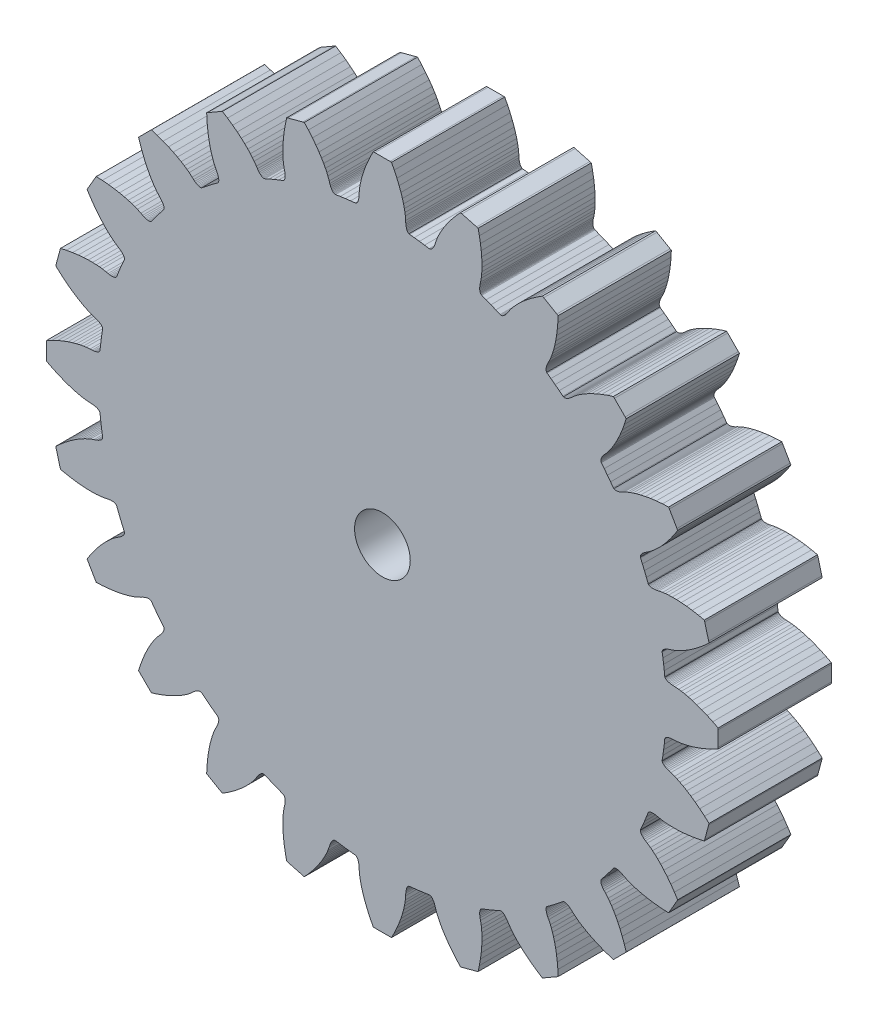
SolidWorks part; units mm, degrees
ref_plane "Front Plane" through (0, 0, 0) normal (0, 0, 1) x (1, 0, 0)
ref_plane "Top Plane" through (0, 0, 0) normal (0, 1, 0) x (1, 0, 0)
ref_plane "Right Plane" through (0, 0, 0) normal (1, 0, 0) x (0, 0, -1)
sketch "Sketch2" plane through (0, 0, 0) normal (0, 0, 1) x (1, 0, 0)
  line L1176 (14.3718, 15.6808) -> (14.3718, 14.9799) construction
  line L1177 (14.3718, 14.9799) -> (14.0889, 12.877) construction
  line L1178 (14.0889, 12.877) -> (13.2783, 10.2659) construction
  line L1179 (13.2783, 10.2659) -> (11.9955, 7.9026) construction
  line L1180 (11.9955, 7.9026) -> (10.297, 5.8436) construction
  line L1181 (10.297, 5.8436) -> (8.2381, 4.1454) construction
  line L1182 (8.2381, 4.1454) -> (5.8748, 2.8624) construction
  line L1183 (5.8748, 2.8624) -> (3.2636, 2.0519) construction
  line L1184 (3.2636, 2.0519) -> (1.1609, 1.7689) construction
  line L1185 (1.1609, 1.7689) -> (0.46, 1.7689) construction
  line L1186 (0.46, 1.7689) -> (-0.2414, 1.7689) construction
  line L1187 (-0.2414, 1.7689) -> (-2.3442, 2.0519) construction
  line L1188 (-2.3442, 2.0519) -> (-4.9553, 2.8624) construction
  line L1189 (-4.9553, 2.8624) -> (-7.3186, 4.1454) construction
  line L1190 (-7.3186, 4.1454) -> (-9.3776, 5.8436) construction
  line L1191 (-9.3776, 5.8436) -> (-11.0759, 7.9026) construction
  line L1192 (-11.0759, 7.9026) -> (-12.3588, 10.2659) construction
  line L1193 (-12.3588, 10.2659) -> (-13.1694, 12.877) construction
  line L1194 (-13.1694, 12.877) -> (-13.4517, 14.9799) construction
  line L1195 (-13.4517, 14.9799) -> (-13.4517, 15.6808) construction
  line L1196 (-13.4517, 15.6808) -> (-13.4517, 16.3821) construction
  line L1197 (-13.4517, 16.3821) -> (-13.1694, 18.485) construction
  line L1198 (-13.1694, 18.485) -> (-12.3588, 21.096) construction
  line L1199 (-12.3588, 21.096) -> (-11.0759, 23.4593) construction
  line L1200 (-11.0759, 23.4593) -> (-9.3776, 25.5185) construction
  line L1201 (-9.3776, 25.5185) -> (-7.3186, 27.2167) construction
  line L1202 (-7.3186, 27.2167) -> (-4.9553, 28.4995) construction
  line L1203 (-4.9553, 28.4995) -> (-2.3442, 29.3101) construction
  line L1204 (-2.3442, 29.3101) -> (-0.2414, 29.5925) construction
  line L1205 (-0.2414, 29.5925) -> (0.46, 29.5925) construction
  line L1206 (0.46, 29.5925) -> (1.1609, 29.5925) construction
  line L1207 (1.1609, 29.5925) -> (3.2636, 29.3101) construction
  line L1208 (3.2636, 29.3101) -> (5.8748, 28.4995) construction
  line L1209 (5.8748, 28.4995) -> (8.2381, 27.2167) construction
  line L1210 (8.2381, 27.2167) -> (10.297, 25.5185) construction
  line L1211 (10.297, 25.5185) -> (11.9955, 23.4593) construction
  line L1212 (11.9955, 23.4593) -> (13.2783, 21.096) construction
  line L1213 (13.2783, 21.096) -> (14.0889, 18.485) construction
  line L1214 (14.0889, 18.485) -> (14.3718, 16.3821) construction
  line L1215 (14.3718, 16.3821) -> (14.3718, 15.6808) construction
  line L1216 (15.5311, 15.6808) -> (15.5311, 14.9215) construction
  line L1217 (15.5311, 14.9215) -> (15.2244, 12.6436) construction
  line L1218 (15.2244, 12.6436) -> (14.3467, 9.8142) construction
  line L1219 (14.3467, 9.8142) -> (12.9571, 7.2546) construction
  line L1220 (12.9571, 7.2546) -> (11.1171, 5.0237) construction
  line L1221 (11.1171, 5.0237) -> (8.8862, 3.1836) construction
  line L1222 (8.8862, 3.1836) -> (6.3266, 1.794) construction
  line L1223 (6.3266, 1.794) -> (3.4972, 0.9163) construction
  line L1224 (3.4972, 0.9163) -> (1.2192, 0.6096) construction
  line L1225 (1.2192, 0.6096) -> (0.46, 0.6096) construction
  line L1226 (0.46, 0.6096) -> (-0.2997, 0.6096) construction
  line L1227 (-0.2997, 0.6096) -> (-2.5776, 0.9163) construction
  line L1228 (-2.5776, 0.9163) -> (-5.4064, 1.794) construction
  line L1229 (-5.4064, 1.794) -> (-7.9667, 3.1836) construction
  line L1230 (-7.9667, 3.1836) -> (-10.1969, 5.0237) construction
  line L1231 (-10.1969, 5.0237) -> (-12.0376, 7.2546) construction
  line L1232 (-12.0376, 7.2546) -> (-13.4272, 9.8142) construction
  line L1233 (-13.4272, 9.8142) -> (-14.3049, 12.6436) construction
  line L1234 (-14.3049, 12.6436) -> (-14.6111, 14.9215) construction
  line L1235 (-14.6111, 14.9215) -> (-14.6111, 15.6808) construction
  line L1236 (-14.6111, 15.6808) -> (-14.6111, 16.4404) construction
  line L1237 (-14.6111, 16.4404) -> (-14.3049, 18.7184) construction
  line L1238 (-14.3049, 18.7184) -> (-13.4272, 21.5472) construction
  line L1239 (-13.4272, 21.5472) -> (-12.0376, 24.1074) construction
  line L1240 (-12.0376, 24.1074) -> (-10.1969, 26.3376) construction
  line L1241 (-10.1969, 26.3376) -> (-7.9667, 28.1784) construction
  line L1242 (-7.9667, 28.1784) -> (-5.4064, 29.5679) construction
  line L1243 (-5.4064, 29.5679) -> (-2.5776, 30.4456) construction
  line L1244 (-2.5776, 30.4456) -> (-0.2997, 30.7518) construction
  line L1245 (-0.2997, 30.7518) -> (0.46, 30.7518) construction
  line L1246 (0.46, 30.7518) -> (1.2192, 30.7518) construction
  line L1247 (1.2192, 30.7518) -> (3.4972, 30.4456) construction
  line L1248 (3.4972, 30.4456) -> (6.3266, 29.5679) construction
  line L1249 (6.3266, 29.5679) -> (8.8862, 28.1784) construction
  line L1250 (8.8862, 28.1784) -> (11.1171, 26.3376) construction
  line L1251 (11.1171, 26.3376) -> (12.9571, 24.1074) construction
  line L1252 (12.9571, 24.1074) -> (14.3467, 21.5472) construction
  line L1253 (14.3467, 21.5472) -> (15.2244, 18.7184) construction
  line L1254 (15.2244, 18.7184) -> (15.5311, 16.4404) construction
  line L1255 (15.5311, 16.4404) -> (15.5311, 15.6808) construction
  line L1256 (0.46, 16.0747) -> (0.46, 15.2868) construction
  line L1257 (0.0661, 15.6808) -> (0.8541, 15.6808) construction
  line L1282 (14.9176, 19.0032) -> (14.7005, 18.8219)
  line L1283 (14.7005, 18.8219) -> (14.4954, 18.6638)
  line L1284 (14.4954, 18.6638) -> (14.3022, 18.5276)
  line L1285 (14.3022, 18.5276) -> (14.1234, 18.4128)
  line L1286 (14.1234, 18.4128) -> (13.9584, 18.3162)
  line L1287 (13.9584, 18.3162) -> (13.8103, 18.2372)
  line L1288 (13.8103, 18.2372) -> (13.6811, 18.1757)
  line L1289 (13.6811, 18.1757) -> (13.5682, 18.1274)
  line L1290 (13.5682, 18.1274) -> (13.4038, 18.0684)
  line L1291 (13.4038, 18.0684) -> (13.3152, 18.0408)
  line L1292 (13.3152, 18.0408) -> (13.2551, 18.0182)
  line L1293 (13.2551, 18.0182) -> (13.2018, 17.9944)
  line L1294 (13.2018, 17.9944) -> (13.1553, 17.9693)
  line L1295 (13.1553, 17.9693) -> (13.1152, 17.9435)
  line L1296 (13.1152, 17.9435) -> (13.0819, 17.9172)
  line L1297 (13.0819, 17.9172) -> (13.0549, 17.8902)
  line L1298 (13.0549, 17.8902) -> (13.0348, 17.8639)
  line L1299 (13.0348, 17.8639) -> (13.0217, 17.8375)
  line L1300 (13.0217, 17.8375) -> (13.0148, 17.8111)
  line L1301 (13.0148, 17.8111) -> (13.0154, 17.7805)
  line L1302 (13.0154, 17.7805) -> (13.048, 17.5735)
  line L1303 (13.048, 17.5735) -> (13.0806, 17.3419)
  line L1304 (13.0806, 17.3419) -> (13.1089, 17.1105)
  line L1305 (13.1089, 17.1105) -> (13.1309, 16.9021)
  line L1306 (13.1309, 16.9021) -> (13.1384, 16.8715)
  line L1307 (13.1384, 16.8715) -> (13.1516, 16.8482)
  line L1308 (13.1516, 16.8482) -> (13.1717, 16.8261)
  line L1309 (13.1717, 16.8261) -> (13.1981, 16.8061)
  line L1310 (13.1981, 16.8061) -> (13.2307, 16.7873)
  line L1311 (13.2307, 16.7873) -> (13.2695, 16.7704)
  line L1312 (13.2695, 16.7704) -> (13.3152, 16.756)
  line L1313 (13.3152, 16.756) -> (13.3668, 16.7435)
  line L1314 (13.3668, 16.7435) -> (13.4245, 16.7347)
  line L1315 (13.4245, 16.7347) -> (13.488, 16.7283)
  line L1316 (13.488, 16.7283) -> (13.5807, 16.7246)
  line L1317 (13.5807, 16.7246) -> (13.7552, 16.7103)
  line L1318 (13.7552, 16.7103) -> (13.8763, 16.6926)
  line L1319 (13.8763, 16.6926) -> (14.0172, 16.6662)
  line L1320 (14.0172, 16.6662) -> (14.1811, 16.6286)
  line L1321 (14.1811, 16.6286) -> (14.365, 16.5779)
  line L1322 (14.365, 16.5779) -> (14.5676, 16.5125)
  line L1323 (14.5676, 16.5125) -> (14.7896, 16.4316)
  line L1324 (14.7896, 16.4316) -> (15.0286, 16.3318)
  line L1325 (15.0286, 16.3318) -> (15.2846, 16.2127)
  line L1326 (15.2846, 16.2127) -> (15.5255, 16.0885)
  line L1327 (15.5255, 16.0885) -> (15.5274, 16.0207)
  line L1328 (15.5274, 16.0207) -> (15.5274, 15.3406)
  line L1329 (15.5274, 15.3406) -> (15.5255, 15.2723)
  line L1330 (15.5255, 15.2723) -> (15.2846, 15.1486)
  line L1331 (15.2846, 15.1486) -> (15.0286, 15.0295)
  line L1332 (15.0286, 15.0295) -> (14.7896, 14.9297)
  line L1333 (14.7896, 14.9297) -> (14.5676, 14.8482)
  line L1334 (14.5676, 14.8482) -> (14.365, 14.7836)
  line L1335 (14.365, 14.7836) -> (14.1811, 14.7327)
  line L1336 (14.1811, 14.7327) -> (14.0172, 14.6951)
  line L1337 (14.0172, 14.6951) -> (13.8763, 14.6687)
  line L1338 (13.8763, 14.6687) -> (13.7552, 14.6512)
  line L1339 (13.7552, 14.6512) -> (13.5807, 14.6368)
  line L1340 (13.5807, 14.6368) -> (13.488, 14.633)
  line L1341 (13.488, 14.633) -> (13.4245, 14.6266)
  line L1342 (13.4245, 14.6266) -> (13.3668, 14.6174)
  line L1343 (13.3668, 14.6174) -> (13.3152, 14.6054)
  line L1344 (13.3152, 14.6054) -> (13.2695, 14.5909)
  line L1345 (13.2695, 14.5909) -> (13.2307, 14.574)
  line L1346 (13.2307, 14.574) -> (13.1981, 14.5552)
  line L1347 (13.1981, 14.5552) -> (13.1717, 14.5345)
  line L1348 (13.1717, 14.5345) -> (13.1516, 14.5125)
  line L1349 (13.1516, 14.5125) -> (13.1384, 14.4894)
  line L1350 (13.1384, 14.4894) -> (13.1309, 14.4592)
  line L1351 (13.1309, 14.4592) -> (13.1089, 14.2509)
  line L1352 (13.1089, 14.2509) -> (13.0806, 14.0187)
  line L1353 (13.0806, 14.0187) -> (13.048, 13.7879)
  line L1354 (13.048, 13.7879) -> (13.0154, 13.5809)
  line L1355 (13.0154, 13.5809) -> (13.0148, 13.5495)
  line L1356 (13.0148, 13.5495) -> (13.0217, 13.5238)
  line L1357 (13.0217, 13.5238) -> (13.0348, 13.4975)
  line L1358 (13.0348, 13.4975) -> (13.0549, 13.4711)
  line L1359 (13.0549, 13.4711) -> (13.0819, 13.4442)
  line L1360 (13.0819, 13.4442) -> (13.1152, 13.4178)
  line L1361 (13.1152, 13.4178) -> (13.1553, 13.3921)
  line L1362 (13.1553, 13.3921) -> (13.2018, 13.367)
  line L1363 (13.2018, 13.367) -> (13.2551, 13.3431)
  line L1364 (13.2551, 13.3431) -> (13.3152, 13.3205)
  line L1365 (13.3152, 13.3205) -> (13.4038, 13.2929)
  line L1366 (13.4038, 13.2929) -> (13.5682, 13.2339)
  line L1367 (13.5682, 13.2339) -> (13.6811, 13.1857)
  line L1368 (13.6811, 13.1857) -> (13.8103, 13.1236)
  line L1369 (13.8103, 13.1236) -> (13.9584, 13.0451)
  line L1370 (13.9584, 13.0451) -> (14.1234, 12.9485)
  line L1371 (14.1234, 12.9485) -> (14.3022, 12.8331)
  line L1372 (14.3022, 12.8331) -> (14.4954, 12.6969)
  line L1373 (14.4954, 12.6969) -> (14.7005, 12.5394)
  line L1374 (14.7005, 12.5394) -> (14.9176, 12.3575)
  line L1375 (14.9176, 12.3575) -> (15.1177, 12.1756)
  line L1376 (15.1177, 12.1756) -> (15.1013, 12.1097)
  line L1377 (15.1013, 12.1097) -> (14.9258, 11.4522)
  line L1378 (14.9258, 11.4522) -> (14.9064, 11.387)
  line L1379 (14.9064, 11.387) -> (14.6421, 11.3299)
  line L1380 (14.6421, 11.3299) -> (14.3637, 11.281)
  line L1381 (14.3637, 11.281) -> (14.1071, 11.2465)
  line L1382 (14.1071, 11.2465) -> (13.8711, 11.2251)
  line L1383 (13.8711, 11.2251) -> (13.6591, 11.2152)
  line L1384 (13.6591, 11.2152) -> (13.4679, 11.2139)
  line L1385 (13.4679, 11.2139) -> (13.3003, 11.2196)
  line L1386 (13.3003, 11.2196) -> (13.1573, 11.2308)
  line L1387 (13.1573, 11.2308) -> (13.0355, 11.2452)
  line L1388 (13.0355, 11.2452) -> (12.8637, 11.2766)
  line L1389 (12.8637, 11.2766) -> (12.7725, 11.2967)
  line L1390 (12.7725, 11.2967) -> (12.71, 11.3073)
  line L1391 (12.71, 11.3073) -> (12.6517, 11.313)
  line L1392 (12.6517, 11.313) -> (12.5989, 11.3148)
  line L1393 (12.5989, 11.3148) -> (12.5513, 11.3123)
  line L1394 (12.5513, 11.3123) -> (12.5092, 11.3067)
  line L1395 (12.5092, 11.3067) -> (12.4727, 11.2967)
  line L1396 (12.4727, 11.2967) -> (12.4421, 11.2835)
  line L1397 (12.4421, 11.2835) -> (12.417, 11.2678)
  line L1398 (12.417, 11.2678) -> (12.398, 11.2484)
  line L1399 (12.398, 11.2484) -> (12.3831, 11.2214)
  line L1400 (12.3831, 11.2214) -> (12.3078, 11.0256)
  line L1401 (12.3078, 11.0256) -> (12.2206, 10.8092)
  line L1402 (12.2206, 10.8092) -> (12.1297, 10.5947)
  line L1403 (12.1297, 10.5947) -> (12.0443, 10.4027)
  line L1404 (12.0443, 10.4027) -> (12.0356, 10.3732)
  line L1405 (12.0356, 10.3732) -> (12.0356, 10.3462)
  line L1406 (12.0356, 10.3462) -> (12.0418, 10.3174)
  line L1407 (12.0418, 10.3174) -> (12.0543, 10.286)
  line L1408 (12.0543, 10.286) -> (12.0732, 10.2534)
  line L1409 (12.0732, 10.2534) -> (12.0982, 10.2195)
  line L1410 (12.0982, 10.2195) -> (12.1302, 10.1844)
  line L1411 (12.1302, 10.1844) -> (12.1692, 10.148)
  line L1412 (12.1692, 10.148) -> (12.2144, 10.111)
  line L1413 (12.2144, 10.111) -> (12.2664, 10.0739)
  line L1414 (12.2664, 10.0739) -> (12.3447, 10.0244)
  line L1415 (12.3447, 10.0244) -> (12.4884, 9.9246)
  line L1416 (12.4884, 9.9246) -> (12.5845, 9.8487)
  line L1417 (12.5845, 9.8487) -> (12.6936, 9.7559)
  line L1418 (12.6936, 9.7559) -> (12.8166, 9.6411)
  line L1419 (12.8166, 9.6411) -> (12.9509, 9.5049)
  line L1420 (12.9509, 9.5049) -> (13.0938, 9.3475)
  line L1421 (13.0938, 9.3475) -> (13.245, 9.1662)
  line L1422 (13.245, 9.1662) -> (13.4025, 8.9604)
  line L1423 (13.4025, 8.9604) -> (13.5644, 8.7289)
  line L1424 (13.5644, 8.7289) -> (13.7112, 8.5011)
  line L1425 (13.7112, 8.5011) -> (13.6786, 8.4415)
  line L1426 (13.6786, 8.4415) -> (13.3386, 7.8531)
  line L1427 (13.3386, 7.8531) -> (13.3034, 7.7947)
  line L1428 (13.3034, 7.7947) -> (13.0325, 7.8073)
  line L1429 (13.0325, 7.8073) -> (12.7514, 7.8324)
  line L1430 (12.7514, 7.8324) -> (12.4941, 7.8656)
  line L1431 (12.4941, 7.8656) -> (12.2614, 7.9064)
  line L1432 (12.2614, 7.9064) -> (12.0538, 7.951)
  line L1433 (12.0538, 7.951) -> (11.8687, 7.9993)
  line L1434 (11.8687, 7.9993) -> (11.7081, 8.0488)
  line L1435 (11.7081, 8.0488) -> (11.5726, 8.0965)
  line L1436 (11.5726, 8.0965) -> (11.459, 8.1417)
  line L1437 (11.459, 8.1417) -> (11.3009, 8.2163)
  line L1438 (11.3009, 8.2163) -> (11.2188, 8.2596)
  line L1439 (11.2188, 8.2596) -> (11.1602, 8.286)
  line L1440 (11.1602, 8.286) -> (11.1059, 8.3067)
  line L1441 (11.1059, 8.3067) -> (11.0549, 8.3217)
  line L1442 (11.0549, 8.3217) -> (11.0085, 8.3318)
  line L1443 (11.0085, 8.3318) -> (10.9664, 8.3368)
  line L1444 (10.9664, 8.3368) -> (10.9289, 8.3368)
  line L1445 (10.9289, 8.3368) -> (10.8956, 8.3324)
  line L1446 (10.8956, 8.3324) -> (10.8673, 8.3236)
  line L1447 (10.8673, 8.3236) -> (10.8442, 8.3098)
  line L1448 (10.8442, 8.3098) -> (10.8228, 8.2872)
  line L1449 (10.8228, 8.2872) -> (10.6998, 8.1178)
  line L1450 (10.6998, 8.1178) -> (10.5593, 7.9315)
  line L1451 (10.5593, 7.9315) -> (10.4157, 7.7477)
  line L1452 (10.4157, 7.7477) -> (10.2833, 7.5846)
  line L1453 (10.2833, 7.5846) -> (10.2677, 7.5582)
  line L1454 (10.2677, 7.5582) -> (10.2601, 7.5319)
  line L1455 (10.2601, 7.5319) -> (10.2589, 7.5024)
  line L1456 (10.2589, 7.5024) -> (10.2627, 7.4691)
  line L1457 (10.2627, 7.4691) -> (10.2726, 7.4328)
  line L1458 (10.2726, 7.4328) -> (10.2884, 7.3932)
  line L1459 (10.2884, 7.3932) -> (10.3102, 7.3512)
  line L1460 (10.3102, 7.3512) -> (10.3378, 7.306)
  line L1461 (10.3378, 7.306) -> (10.3723, 7.259)
  line L1462 (10.3723, 7.259) -> (10.4131, 7.2094)
  line L1463 (10.4131, 7.2094) -> (10.4759, 7.141)
  line L1464 (10.4759, 7.141) -> (10.5889, 7.0074)
  line L1465 (10.5889, 7.0074) -> (10.6622, 6.9095)
  line L1466 (10.6622, 6.9095) -> (10.7431, 6.791)
  line L1467 (10.7431, 6.791) -> (10.8322, 6.6485)
  line L1468 (10.8322, 6.6485) -> (10.9269, 6.4829)
  line L1469 (10.9269, 6.4829) -> (11.0243, 6.2935)
  line L1470 (11.0243, 6.2935) -> (11.1234, 6.0789)
  line L1471 (11.1234, 6.0789) -> (11.2225, 5.8399)
  line L1472 (11.2225, 5.8399) -> (11.3191, 5.5745)
  line L1473 (11.3191, 5.5745) -> (11.4012, 5.316)
  line L1474 (11.4012, 5.316) -> (11.3542, 5.2671)
  line L1475 (11.3542, 5.2671) -> (10.8736, 4.7865)
  line L1476 (10.8736, 4.7865) -> (10.8248, 4.7395)
  line L1477 (10.8248, 4.7395) -> (10.5662, 4.8217)
  line L1478 (10.5662, 4.8217) -> (10.3008, 4.9183)
  line L1479 (10.3008, 4.9183) -> (10.0619, 5.0174)
  line L1480 (10.0619, 5.0174) -> (9.8473, 5.1165)
  line L1481 (9.8473, 5.1165) -> (9.6578, 5.2138)
  line L1482 (9.6578, 5.2138) -> (9.4922, 5.3085)
  line L1483 (9.4922, 5.3085) -> (9.3497, 5.3976)
  line L1484 (9.3497, 5.3976) -> (9.2312, 5.4785)
  line L1485 (9.2312, 5.4785) -> (9.1333, 5.5519)
  line L1486 (9.1333, 5.5519) -> (8.9997, 5.6648)
  line L1487 (8.9997, 5.6648) -> (8.9313, 5.7276)
  line L1488 (8.9313, 5.7276) -> (8.8818, 5.7684)
  line L1489 (8.8818, 5.7684) -> (8.8347, 5.8029)
  line L1490 (8.8347, 5.8029) -> (8.7896, 5.8305)
  line L1491 (8.7896, 5.8305) -> (8.7475, 5.8524)
  line L1492 (8.7475, 5.8524) -> (8.708, 5.8681)
  line L1493 (8.708, 5.8681) -> (8.6715, 5.8782)
  line L1494 (8.6715, 5.8782) -> (8.6384, 5.8819)
  line L1495 (8.6384, 5.8819) -> (8.6089, 5.8807)
  line L1496 (8.6089, 5.8807) -> (8.5826, 5.8731)
  line L1497 (8.5826, 5.8731) -> (8.5563, 5.8575)
  line L1498 (8.5563, 5.8575) -> (8.3931, 5.7251)
  line L1499 (8.3931, 5.7251) -> (8.2091, 5.5814)
  line L1500 (8.2091, 5.5814) -> (8.0228, 5.4409)
  line L1501 (8.0228, 5.4409) -> (7.8537, 5.3179)
  line L1502 (7.8537, 5.3179) -> (7.831, 5.2966)
  line L1503 (7.831, 5.2966) -> (7.8171, 5.2734)
  line L1504 (7.8171, 5.2734) -> (7.8083, 5.2451)
  line L1505 (7.8083, 5.2451) -> (7.8039, 5.2119)
  line L1506 (7.8039, 5.2119) -> (7.8039, 5.1743)
  line L1507 (7.8039, 5.1743) -> (7.8089, 5.1322)
  line L1508 (7.8089, 5.1322) -> (7.8191, 5.0858)
  line L1509 (7.8191, 5.0858) -> (7.834, 5.035)
  line L1510 (7.834, 5.035) -> (7.8547, 4.9804)
  line L1511 (7.8547, 4.9804) -> (7.8811, 4.922)
  line L1512 (7.8811, 4.922) -> (7.9244, 4.8399)
  line L1513 (7.9244, 4.8399) -> (7.9991, 4.6818)
  line L1514 (7.9991, 4.6818) -> (8.0442, 4.5682)
  line L1515 (8.0442, 4.5682) -> (8.092, 4.4327)
  line L1516 (8.092, 4.4327) -> (8.1416, 4.2721)
  line L1517 (8.1416, 4.2721) -> (8.1897, 4.087)
  line L1518 (8.1897, 4.087) -> (8.2344, 3.8794)
  line L1519 (8.2344, 3.8794) -> (8.2751, 3.6466)
  line L1520 (8.2751, 3.6466) -> (8.3084, 3.3894)
  line L1521 (8.3084, 3.3894) -> (8.3334, 3.1084)
  line L1522 (8.3334, 3.1084) -> (8.346, 2.8373)
  line L1523 (8.346, 2.8373) -> (8.2877, 2.8022)
  line L1524 (8.2877, 2.8022) -> (7.6993, 2.4622)
  line L1525 (7.6993, 2.4622) -> (7.6397, 2.4295)
  line L1526 (7.6397, 2.4295) -> (7.4119, 2.5763)
  line L1527 (7.4119, 2.5763) -> (7.1803, 2.7382)
  line L1528 (7.1803, 2.7382) -> (6.9746, 2.8957)
  line L1529 (6.9746, 2.8957) -> (6.7933, 3.0469)
  line L1530 (6.7933, 3.0469) -> (6.6359, 3.1899)
  line L1531 (6.6359, 3.1899) -> (6.4997, 3.3242)
  line L1532 (6.4997, 3.3242) -> (6.3849, 3.4471)
  line L1533 (6.3849, 3.4471) -> (6.292, 3.5563)
  line L1534 (6.292, 3.5563) -> (6.216, 3.6523)
  line L1535 (6.216, 3.6523) -> (6.1163, 3.7959)
  line L1536 (6.1163, 3.7959) -> (6.0669, 3.8744)
  line L1537 (6.0669, 3.8744) -> (6.0297, 3.9264)
  line L1538 (6.0297, 3.9264) -> (5.9928, 3.9716)
  line L1539 (5.9928, 3.9716) -> (5.9564, 4.0105)
  line L1540 (5.9564, 4.0105) -> (5.9212, 4.0425)
  line L1541 (5.9212, 4.0425) -> (5.8873, 4.0676)
  line L1542 (5.8873, 4.0676) -> (5.8547, 4.0864)
  line L1543 (5.8547, 4.0864) -> (5.8234, 4.0989)
  line L1544 (5.8234, 4.0989) -> (5.7945, 4.1052)
  line L1545 (5.7945, 4.1052) -> (5.7675, 4.1052)
  line L1546 (5.7675, 4.1052) -> (5.7381, 4.0964)
  line L1547 (5.7381, 4.0964) -> (5.546, 4.0111)
  line L1548 (5.546, 4.0111) -> (5.3314, 3.9202)
  line L1549 (5.3314, 3.9202) -> (5.1152, 3.8329)
  line L1550 (5.1152, 3.8329) -> (4.9194, 3.7577)
  line L1551 (4.9194, 3.7577) -> (4.8923, 3.7426)
  line L1552 (4.8923, 3.7426) -> (4.8729, 3.7238)
  line L1553 (4.8729, 3.7238) -> (4.8572, 3.6987)
  line L1554 (4.8572, 3.6987) -> (4.844, 3.668)
  line L1555 (4.844, 3.668) -> (4.8341, 3.6316)
  line L1556 (4.8341, 3.6316) -> (4.8284, 3.5895)
  line L1557 (4.8284, 3.5895) -> (4.8259, 3.5419)
  line L1558 (4.8259, 3.5419) -> (4.8278, 3.4892)
  line L1559 (4.8278, 3.4892) -> (4.8334, 3.4308)
  line L1560 (4.8334, 3.4308) -> (4.844, 3.3681)
  line L1561 (4.844, 3.3681) -> (4.8641, 3.2771)
  line L1562 (4.8641, 3.2771) -> (4.8956, 3.1052)
  line L1563 (4.8956, 3.1052) -> (4.9099, 2.9835)
  line L1564 (4.9099, 2.9835) -> (4.9213, 2.8405)
  line L1565 (4.9213, 2.8405) -> (4.9269, 2.6729)
  line L1566 (4.9269, 2.6729) -> (4.9256, 2.4816)
  line L1567 (4.9256, 2.4816) -> (4.9157, 2.2696)
  line L1568 (4.9157, 2.2696) -> (4.8943, 2.0337)
  line L1569 (4.8943, 2.0337) -> (4.8597, 1.7771)
  line L1570 (4.8597, 1.7771) -> (4.8108, 1.4985)
  line L1571 (4.8108, 1.4985) -> (4.7538, 1.2344)
  line L1572 (4.7538, 1.2344) -> (4.6886, 1.215)
  line L1573 (4.6886, 1.215) -> (4.0311, 1.0393)
  line L1574 (4.0311, 1.0393) -> (3.9652, 1.023)
  line L1575 (3.9652, 1.023) -> (3.7833, 1.2231)
  line L1576 (3.7833, 1.2231) -> (3.6013, 1.4402)
  line L1577 (3.6013, 1.4402) -> (3.4439, 1.6453)
  line L1578 (3.4439, 1.6453) -> (3.3077, 1.8386)
  line L1579 (3.3077, 1.8386) -> (3.1922, 2.0174)
  line L1580 (3.1922, 2.0174) -> (3.0957, 2.1824)
  line L1581 (3.0957, 2.1824) -> (3.0171, 2.3304)
  line L1582 (3.0171, 2.3304) -> (2.9551, 2.4596)
  line L1583 (2.9551, 2.4596) -> (2.9068, 2.5726)
  line L1584 (2.9068, 2.5726) -> (2.8479, 2.737)
  line L1585 (2.8479, 2.737) -> (2.8203, 2.8254)
  line L1586 (2.8203, 2.8254) -> (2.7976, 2.8856)
  line L1587 (2.7976, 2.8856) -> (2.7738, 2.939)
  line L1588 (2.7738, 2.939) -> (2.7486, 2.9854)
  line L1589 (2.7486, 2.9854) -> (2.7229, 3.0255)
  line L1590 (2.7229, 3.0255) -> (2.6965, 3.0588)
  line L1591 (2.6965, 3.0588) -> (2.6696, 3.0858)
  line L1592 (2.6696, 3.0858) -> (2.6432, 3.1058)
  line L1593 (2.6432, 3.1058) -> (2.6169, 3.119)
  line L1594 (2.6169, 3.119) -> (2.5912, 3.1259)
  line L1595 (2.5912, 3.1259) -> (2.5599, 3.1253)
  line L1596 (2.5599, 3.1253) -> (2.3529, 3.0927)
  line L1597 (2.3529, 3.0927) -> (2.122, 3.06)
  line L1598 (2.122, 3.06) -> (1.8899, 3.0318)
  line L1599 (1.8899, 3.0318) -> (1.6815, 3.0099)
  line L1600 (1.6815, 3.0099) -> (1.6513, 3.0023)
  line L1601 (1.6513, 3.0023) -> (1.6282, 2.9891)
  line L1602 (1.6282, 2.9891) -> (1.6062, 2.9691)
  line L1603 (1.6062, 2.9691) -> (1.5855, 2.9427)
  line L1604 (1.5855, 2.9427) -> (1.5667, 2.9101)
  line L1605 (1.5667, 2.9101) -> (1.5499, 2.8712)
  line L1606 (1.5499, 2.8712) -> (1.5355, 2.8254)
  line L1607 (1.5355, 2.8254) -> (1.5233, 2.774)
  line L1608 (1.5233, 2.774) -> (1.5141, 2.7162)
  line L1609 (1.5141, 2.7162) -> (1.5078, 2.6529)
  line L1610 (1.5078, 2.6529) -> (1.5039, 2.56)
  line L1611 (1.5039, 2.56) -> (1.4897, 2.3856)
  line L1612 (1.4897, 2.3856) -> (1.472, 2.2645)
  line L1613 (1.472, 2.2645) -> (1.4456, 2.1234)
  line L1614 (1.4456, 2.1234) -> (1.408, 1.9596)
  line L1615 (1.408, 1.9596) -> (1.3571, 1.7758)
  line L1616 (1.3571, 1.7758) -> (1.2926, 1.5732)
  line L1617 (1.2926, 1.5732) -> (1.211, 1.3511)
  line L1618 (1.211, 1.3511) -> (1.1113, 1.1121)
  line L1619 (1.1113, 1.1121) -> (0.9921, 0.8561)
  line L1620 (0.9921, 0.8561) -> (0.8685, 0.6152)
  line L1621 (0.8685, 0.6152) -> (0.8001, 0.6133)
  line L1622 (0.8001, 0.6133) -> (0.12, 0.6133)
  line L1623 (0.12, 0.6133) -> (0.0522, 0.6152)
  line L1624 (0.0522, 0.6152) -> (-0.0719, 0.8561)
  line L1625 (-0.0719, 0.8561) -> (-0.1911, 1.1121)
  line L1626 (-0.1911, 1.1121) -> (-0.2908, 1.3511)
  line L1627 (-0.2908, 1.3511) -> (-0.3717, 1.5732)
  line L1628 (-0.3717, 1.5732) -> (-0.4372, 1.7758)
  line L1629 (-0.4372, 1.7758) -> (-0.4879, 1.9596)
  line L1630 (-0.4879, 1.9596) -> (-0.5255, 2.1234)
  line L1631 (-0.5255, 2.1234) -> (-0.5519, 2.2645)
  line L1632 (-0.5519, 2.2645) -> (-0.5695, 2.3856)
  line L1633 (-0.5695, 2.3856) -> (-0.5839, 2.56)
  line L1634 (-0.5839, 2.56) -> (-0.5876, 2.6529)
  line L1635 (-0.5876, 2.6529) -> (-0.5939, 2.7162)
  line L1636 (-0.5939, 2.7162) -> (-0.6026, 2.774)
  line L1637 (-0.6026, 2.774) -> (-0.6153, 2.8254)
  line L1638 (-0.6153, 2.8254) -> (-0.6297, 2.8712)
  line L1639 (-0.6297, 2.8712) -> (-0.6466, 2.9101)
  line L1640 (-0.6466, 2.9101) -> (-0.6654, 2.9427)
  line L1641 (-0.6654, 2.9427) -> (-0.6854, 2.9691)
  line L1642 (-0.6854, 2.9691) -> (-0.7075, 2.9891)
  line L1643 (-0.7075, 2.9891) -> (-0.7307, 3.0023)
  line L1644 (-0.7307, 3.0023) -> (-0.7614, 3.0099)
  line L1645 (-0.7614, 3.0099) -> (-0.9697, 3.0318)
  line L1646 (-0.9697, 3.0318) -> (-1.2012, 3.06)
  line L1647 (-1.2012, 3.06) -> (-1.4327, 3.0927)
  line L1648 (-1.4327, 3.0927) -> (-1.6397, 3.1253)
  line L1649 (-1.6397, 3.1253) -> (-1.6704, 3.1259)
  line L1650 (-1.6704, 3.1259) -> (-1.6968, 3.119)
  line L1651 (-1.6968, 3.119) -> (-1.7232, 3.1058)
  line L1652 (-1.7232, 3.1058) -> (-1.7495, 3.0858)
  line L1653 (-1.7495, 3.0858) -> (-1.7765, 3.0588)
  line L1654 (-1.7765, 3.0588) -> (-1.8028, 3.0255)
  line L1655 (-1.8028, 3.0255) -> (-1.8286, 2.9854)
  line L1656 (-1.8286, 2.9854) -> (-1.8537, 2.939)
  line L1657 (-1.8537, 2.939) -> (-1.8775, 2.8856)
  line L1658 (-1.8775, 2.8856) -> (-1.9001, 2.8254)
  line L1659 (-1.9001, 2.8254) -> (-1.9277, 2.737)
  line L1660 (-1.9277, 2.737) -> (-1.9867, 2.5726)
  line L1661 (-1.9867, 2.5726) -> (-2.0349, 2.4596)
  line L1662 (-2.0349, 2.4596) -> (-2.0964, 2.3304)
  line L1663 (-2.0964, 2.3304) -> (-2.1755, 2.1824)
  line L1664 (-2.1755, 2.1824) -> (-2.2721, 2.0174)
  line L1665 (-2.2721, 2.0174) -> (-2.3869, 1.8386)
  line L1666 (-2.3869, 1.8386) -> (-2.523, 1.6453)
  line L1667 (-2.523, 1.6453) -> (-2.6812, 1.4402)
  line L1668 (-2.6812, 1.4402) -> (-2.8624, 1.2231)
  line L1669 (-2.8624, 1.2231) -> (-3.045, 1.023)
  line L1670 (-3.045, 1.023) -> (-3.1115, 1.0393)
  line L1671 (-3.1115, 1.0393) -> (-3.7684, 1.215)
  line L1672 (-3.7684, 1.215) -> (-3.833, 1.2344)
  line L1673 (-3.833, 1.2344) -> (-3.8907, 1.4985)
  line L1674 (-3.8907, 1.4985) -> (-3.9397, 1.7771)
  line L1675 (-3.9397, 1.7771) -> (-3.9735, 2.0337)
  line L1676 (-3.9735, 2.0337) -> (-3.9948, 2.2696)
  line L1677 (-3.9948, 2.2696) -> (-4.0054, 2.4816)
  line L1678 (-4.0054, 2.4816) -> (-4.0067, 2.6729)
  line L1679 (-4.0067, 2.6729) -> (-4.0005, 2.8405)
  line L1680 (-4.0005, 2.8405) -> (-3.9898, 2.9835)
  line L1681 (-3.9898, 2.9835) -> (-3.9748, 3.1052)
  line L1682 (-3.9748, 3.1052) -> (-3.944, 3.2771)
  line L1683 (-3.944, 3.2771) -> (-3.9233, 3.3681)
  line L1684 (-3.9233, 3.3681) -> (-3.9133, 3.4308)
  line L1685 (-3.9133, 3.4308) -> (-3.907, 3.4892)
  line L1686 (-3.907, 3.4892) -> (-3.9058, 3.5419)
  line L1687 (-3.9058, 3.5419) -> (-3.9076, 3.5895)
  line L1688 (-3.9076, 3.5895) -> (-3.9139, 3.6316)
  line L1689 (-3.9139, 3.6316) -> (-3.9239, 3.668)
  line L1690 (-3.9239, 3.668) -> (-3.9365, 3.6987)
  line L1691 (-3.9365, 3.6987) -> (-3.9528, 3.7238)
  line L1692 (-3.9528, 3.7238) -> (-3.9717, 3.7426)
  line L1693 (-3.9717, 3.7426) -> (-3.9992, 3.7577)
  line L1694 (-3.9992, 3.7577) -> (-4.195, 3.8329)
  line L1695 (-4.195, 3.8329) -> (-4.4114, 3.9202)
  line L1696 (-4.4114, 3.9202) -> (-4.6259, 4.0111)
  line L1697 (-4.6259, 4.0111) -> (-4.8173, 4.0964)
  line L1698 (-4.8173, 4.0964) -> (-4.8474, 4.1052)
  line L1699 (-4.8474, 4.1052) -> (-4.8744, 4.1052)
  line L1700 (-4.8744, 4.1052) -> (-4.9032, 4.0989)
  line L1701 (-4.9032, 4.0989) -> (-4.934, 4.0864)
  line L1702 (-4.934, 4.0864) -> (-4.9666, 4.0676)
  line L1703 (-4.9666, 4.0676) -> (-5.0011, 4.0425)
  line L1704 (-5.0011, 4.0425) -> (-5.0363, 4.0105)
  line L1705 (-5.0363, 4.0105) -> (-5.0726, 3.9716)
  line L1706 (-5.0726, 3.9716) -> (-5.109, 3.9264)
  line L1707 (-5.109, 3.9264) -> (-5.1467, 3.8744)
  line L1708 (-5.1467, 3.8744) -> (-5.1962, 3.7959)
  line L1709 (-5.1962, 3.7959) -> (-5.296, 3.6523)
  line L1710 (-5.296, 3.6523) -> (-5.3713, 3.5563)
  line L1711 (-5.3713, 3.5563) -> (-5.4647, 3.4471)
  line L1712 (-5.4647, 3.4471) -> (-5.5796, 3.3242)
  line L1713 (-5.5796, 3.3242) -> (-5.7151, 3.1899)
  line L1714 (-5.7151, 3.1899) -> (-5.8725, 3.0469)
  line L1715 (-5.8725, 3.0469) -> (-6.0545, 2.8957)
  line L1716 (-6.0545, 2.8957) -> (-6.2596, 2.7382)
  line L1717 (-6.2596, 2.7382) -> (-6.4911, 2.5763)
  line L1718 (-6.4911, 2.5763) -> (-6.7195, 2.4295)
  line L1719 (-6.7195, 2.4295) -> (-6.7797, 2.4622)
  line L1720 (-6.7797, 2.4622) -> (-7.3682, 2.8022)
  line L1721 (-7.3682, 2.8022) -> (-7.4259, 2.8373)
  line L1722 (-7.4259, 2.8373) -> (-7.4127, 3.1084)
  line L1723 (-7.4127, 3.1084) -> (-7.3882, 3.3894)
  line L1724 (-7.3882, 3.3894) -> (-7.3544, 3.6466)
  line L1725 (-7.3544, 3.6466) -> (-7.3142, 3.8794)
  line L1726 (-7.3142, 3.8794) -> (-7.269, 4.087)
  line L1727 (-7.269, 4.087) -> (-7.2207, 4.2721)
  line L1728 (-7.2207, 4.2721) -> (-7.1718, 4.4327)
  line L1729 (-7.1718, 4.4327) -> (-7.1241, 4.5682)
  line L1730 (-7.1241, 4.5682) -> (-7.0789, 4.6818)
  line L1731 (-7.0789, 4.6818) -> (-7.0043, 4.8399)
  line L1732 (-7.0043, 4.8399) -> (-6.961, 4.922)
  line L1733 (-6.961, 4.922) -> (-6.9347, 4.9804)
  line L1734 (-6.9347, 4.9804) -> (-6.914, 5.035)
  line L1735 (-6.914, 5.035) -> (-6.8983, 5.0858)
  line L1736 (-6.8983, 5.0858) -> (-6.8882, 5.1322)
  line L1737 (-6.8882, 5.1322) -> (-6.8832, 5.1743)
  line L1738 (-6.8832, 5.1743) -> (-6.8832, 5.2119)
  line L1739 (-6.8832, 5.2119) -> (-6.8882, 5.2451)
  line L1740 (-6.8882, 5.2451) -> (-6.897, 5.2734)
  line L1741 (-6.897, 5.2734) -> (-6.9108, 5.2966)
  line L1742 (-6.9108, 5.2966) -> (-6.9328, 5.3179)
  line L1743 (-6.9328, 5.3179) -> (-7.1028, 5.4409)
  line L1744 (-7.1028, 5.4409) -> (-7.2891, 5.5814)
  line L1745 (-7.2891, 5.5814) -> (-7.4729, 5.7251)
  line L1746 (-7.4729, 5.7251) -> (-7.6361, 5.8575)
  line L1747 (-7.6361, 5.8575) -> (-7.6624, 5.8731)
  line L1748 (-7.6624, 5.8731) -> (-7.6881, 5.8807)
  line L1749 (-7.6881, 5.8807) -> (-7.7182, 5.8819)
  line L1750 (-7.7182, 5.8819) -> (-7.7509, 5.8782)
  line L1751 (-7.7509, 5.8782) -> (-7.7872, 5.8681)
  line L1752 (-7.7872, 5.8681) -> (-7.8268, 5.8524)
  line L1753 (-7.8268, 5.8524) -> (-7.8694, 5.8305)
  line L1754 (-7.8694, 5.8305) -> (-7.9146, 5.8029)
  line L1755 (-7.9146, 5.8029) -> (-7.9616, 5.7684)
  line L1756 (-7.9616, 5.7684) -> (-8.0112, 5.7276)
  line L1757 (-8.0112, 5.7276) -> (-8.0796, 5.6648)
  line L1758 (-8.0796, 5.6648) -> (-8.2126, 5.5519)
  line L1759 (-8.2126, 5.5519) -> (-8.3111, 5.4785)
  line L1760 (-8.3111, 5.4785) -> (-8.429, 5.3976)
  line L1761 (-8.429, 5.3976) -> (-8.5715, 5.3085)
  line L1762 (-8.5715, 5.3085) -> (-8.7377, 5.2138)
  line L1763 (-8.7377, 5.2138) -> (-8.9265, 5.1165)
  line L1764 (-8.9265, 5.1165) -> (-9.1411, 5.0174)
  line L1765 (-9.1411, 5.0174) -> (-9.3807, 4.9183)
  line L1766 (-9.3807, 4.9183) -> (-9.6461, 4.8217)
  line L1767 (-9.6461, 4.8217) -> (-9.904, 4.7395)
  line L1768 (-9.904, 4.7395) -> (-9.9535, 4.7865)
  line L1769 (-9.9535, 4.7865) -> (-10.4347, 5.2671)
  line L1770 (-10.4347, 5.2671) -> (-10.4811, 5.316)
  line L1771 (-10.4811, 5.316) -> (-10.399, 5.5745)
  line L1772 (-10.399, 5.5745) -> (-10.3017, 5.8399)
  line L1773 (-10.3017, 5.8399) -> (-10.2032, 6.0789)
  line L1774 (-10.2032, 6.0789) -> (-10.1035, 6.2935)
  line L1775 (-10.1035, 6.2935) -> (-10.0062, 6.4829)
  line L1776 (-10.0062, 6.4829) -> (-9.9121, 6.6485)
  line L1777 (-9.9121, 6.6485) -> (-9.823, 6.791)
  line L1778 (-9.823, 6.791) -> (-9.7421, 6.9095)
  line L1779 (-9.7421, 6.9095) -> (-9.6687, 7.0074)
  line L1780 (-9.6687, 7.0074) -> (-9.5558, 7.141)
  line L1781 (-9.5558, 7.141) -> (-9.4924, 7.2094)
  line L1782 (-9.4924, 7.2094) -> (-9.4523, 7.259)
  line L1783 (-9.4523, 7.259) -> (-9.4178, 7.306)
  line L1784 (-9.4178, 7.306) -> (-9.3902, 7.3512)
  line L1785 (-9.3902, 7.3512) -> (-9.3682, 7.3932)
  line L1786 (-9.3682, 7.3932) -> (-9.3525, 7.4328)
  line L1787 (-9.3525, 7.4328) -> (-9.3425, 7.4691)
  line L1788 (-9.3425, 7.4691) -> (-9.3387, 7.5024)
  line L1789 (-9.3387, 7.5024) -> (-9.34, 7.5319)
  line L1790 (-9.34, 7.5319) -> (-9.3469, 7.5582)
  line L1791 (-9.3469, 7.5582) -> (-9.3632, 7.5846)
  line L1792 (-9.3632, 7.5846) -> (-9.4949, 7.7477)
  line L1793 (-9.4949, 7.7477) -> (-9.6386, 7.9315)
  line L1794 (-9.6386, 7.9315) -> (-9.7791, 8.1178)
  line L1795 (-9.7791, 8.1178) -> (-9.9027, 8.2872)
  line L1796 (-9.9027, 8.2872) -> (-9.924, 8.3098)
  line L1797 (-9.924, 8.3098) -> (-9.9472, 8.3236)
  line L1798 (-9.9472, 8.3236) -> (-9.9755, 8.3324)
  line L1799 (-9.9755, 8.3324) -> (-10.0081, 8.3368)
  line L1800 (-10.0081, 8.3368) -> (-10.0464, 8.3368)
  line L1801 (-10.0464, 8.3368) -> (-10.0884, 8.3318)
  line L1802 (-10.0884, 8.3318) -> (-10.1348, 8.3217)
  line L1803 (-10.1348, 8.3217) -> (-10.1857, 8.3067)
  line L1804 (-10.1857, 8.3067) -> (-10.2402, 8.286)
  line L1805 (-10.2402, 8.286) -> (-10.2986, 8.2596)
  line L1806 (-10.2986, 8.2596) -> (-10.3808, 8.2163)
  line L1807 (-10.3808, 8.2163) -> (-10.5389, 8.1417)
  line L1808 (-10.5389, 8.1417) -> (-10.6524, 8.0965)
  line L1809 (-10.6524, 8.0965) -> (-10.7879, 8.0488)
  line L1810 (-10.7879, 8.0488) -> (-10.9485, 7.9993)
  line L1811 (-10.9485, 7.9993) -> (-11.133, 7.951)
  line L1812 (-11.133, 7.951) -> (-11.3413, 7.9064)
  line L1813 (-11.3413, 7.9064) -> (-11.574, 7.8656)
  line L1814 (-11.574, 7.8656) -> (-11.8306, 7.8324)
  line L1815 (-11.8306, 7.8324) -> (-12.1123, 7.8073)
  line L1816 (-12.1123, 7.8073) -> (-12.3827, 7.7947)
  line L1817 (-12.3827, 7.7947) -> (-12.4184, 7.8531)
  line L1818 (-12.4184, 7.8531) -> (-12.7591, 8.4415)
  line L1819 (-12.7591, 8.4415) -> (-12.7911, 8.5011)
  line L1820 (-12.7911, 8.5011) -> (-12.6443, 8.7289)
  line L1821 (-12.6443, 8.7289) -> (-12.4824, 8.9604)
  line L1822 (-12.4824, 8.9604) -> (-12.325, 9.1662)
  line L1823 (-12.325, 9.1662) -> (-12.1731, 9.3475)
  line L1824 (-12.1731, 9.3475) -> (-12.0301, 9.5049)
  line L1825 (-12.0301, 9.5049) -> (-11.8965, 9.6411)
  line L1826 (-11.8965, 9.6411) -> (-11.7735, 9.7559)
  line L1827 (-11.7735, 9.7559) -> (-11.6643, 9.8487)
  line L1828 (-11.6643, 9.8487) -> (-11.5684, 9.9246)
  line L1829 (-11.5684, 9.9246) -> (-11.4247, 10.0244)
  line L1830 (-11.4247, 10.0244) -> (-11.3463, 10.0739)
  line L1831 (-11.3463, 10.0739) -> (-11.2942, 10.111)
  line L1832 (-11.2942, 10.111) -> (-11.249, 10.148)
  line L1833 (-11.249, 10.148) -> (-11.2101, 10.1844)
  line L1834 (-11.2101, 10.1844) -> (-11.1781, 10.2195)
  line L1835 (-11.1781, 10.2195) -> (-11.1524, 10.2534)
  line L1836 (-11.1524, 10.2534) -> (-11.1336, 10.286)
  line L1837 (-11.1336, 10.286) -> (-11.121, 10.3174)
  line L1838 (-11.121, 10.3174) -> (-11.1148, 10.3462)
  line L1839 (-11.1148, 10.3462) -> (-11.1154, 10.3732)
  line L1840 (-11.1154, 10.3732) -> (-11.1235, 10.4027)
  line L1841 (-11.1235, 10.4027) -> (-11.2095, 10.5947)
  line L1842 (-11.2095, 10.5947) -> (-11.3005, 10.8092)
  line L1843 (-11.3005, 10.8092) -> (-11.3877, 11.0256)
  line L1844 (-11.3877, 11.0256) -> (-11.463, 11.2214)
  line L1845 (-11.463, 11.2214) -> (-11.478, 11.2484)
  line L1846 (-11.478, 11.2484) -> (-11.4968, 11.2678)
  line L1847 (-11.4968, 11.2678) -> (-11.5213, 11.2835)
  line L1848 (-11.5213, 11.2835) -> (-11.552, 11.2967)
  line L1849 (-11.552, 11.2967) -> (-11.5891, 11.3067)
  line L1850 (-11.5891, 11.3067) -> (-11.6311, 11.3123)
  line L1851 (-11.6311, 11.3123) -> (-11.6788, 11.3148)
  line L1852 (-11.6788, 11.3148) -> (-11.7315, 11.313)
  line L1853 (-11.7315, 11.313) -> (-11.7892, 11.3073)
  line L1854 (-11.7892, 11.3073) -> (-11.8526, 11.2967)
  line L1855 (-11.8526, 11.2967) -> (-11.9429, 11.2766)
  line L1856 (-11.9429, 11.2766) -> (-12.1154, 11.2452)
  line L1857 (-12.1154, 11.2452) -> (-12.2365, 11.2308)
  line L1858 (-12.2365, 11.2308) -> (-12.3802, 11.2196)
  line L1859 (-12.3802, 11.2196) -> (-12.5477, 11.2139)
  line L1860 (-12.5477, 11.2139) -> (-12.7384, 11.2152)
  line L1861 (-12.7384, 11.2152) -> (-12.9511, 11.2251)
  line L1862 (-12.9511, 11.2251) -> (-13.1863, 11.2465)
  line L1863 (-13.1863, 11.2465) -> (-13.4435, 11.281)
  line L1864 (-13.4435, 11.281) -> (-13.7215, 11.3299)
  line L1865 (-13.7215, 11.3299) -> (-13.9862, 11.387)
  line L1866 (-13.9862, 11.387) -> (-14.0057, 11.4522)
  line L1867 (-14.0057, 11.4522) -> (-14.182, 12.1097)
  line L1868 (-14.182, 12.1097) -> (-14.1976, 12.1756)
  line L1869 (-14.1976, 12.1756) -> (-13.9969, 12.3575)
  line L1870 (-13.9969, 12.3575) -> (-13.7804, 12.5394)
  line L1871 (-13.7804, 12.5394) -> (-13.5753, 12.6969)
  line L1872 (-13.5753, 12.6969) -> (-13.3821, 12.8331)
  line L1873 (-13.3821, 12.8331) -> (-13.2032, 12.9485)
  line L1874 (-13.2032, 12.9485) -> (-13.0383, 13.0451)
  line L1875 (-13.0383, 13.0451) -> (-12.8902, 13.1236)
  line L1876 (-12.8902, 13.1236) -> (-12.7603, 13.1857)
  line L1877 (-12.7603, 13.1857) -> (-12.648, 13.2339)
  line L1878 (-12.648, 13.2339) -> (-12.4837, 13.2929)
  line L1879 (-12.4837, 13.2929) -> (-12.3946, 13.3205)
  line L1880 (-12.3946, 13.3205) -> (-12.335, 13.3431)
  line L1881 (-12.335, 13.3431) -> (-12.2817, 13.367)
  line L1882 (-12.2817, 13.367) -> (-12.2352, 13.3921)
  line L1883 (-12.2352, 13.3921) -> (-12.1951, 13.4178)
  line L1884 (-12.1951, 13.4178) -> (-12.1618, 13.4442)
  line L1885 (-12.1618, 13.4442) -> (-12.1349, 13.4711)
  line L1886 (-12.1349, 13.4711) -> (-12.1148, 13.4975)
  line L1887 (-12.1148, 13.4975) -> (-12.101, 13.5238)
  line L1888 (-12.101, 13.5238) -> (-12.0947, 13.5495)
  line L1889 (-12.0947, 13.5495) -> (-12.0953, 13.5809)
  line L1890 (-12.0953, 13.5809) -> (-12.128, 13.7879)
  line L1891 (-12.128, 13.7879) -> (-12.1606, 14.0187)
  line L1892 (-12.1606, 14.0187) -> (-12.1888, 14.2509)
  line L1893 (-12.1888, 14.2509) -> (-12.2108, 14.4592)
  line L1894 (-12.2108, 14.4592) -> (-12.2183, 14.4894)
  line L1895 (-12.2183, 14.4894) -> (-12.2315, 14.5125)
  line L1896 (-12.2315, 14.5125) -> (-12.2516, 14.5345)
  line L1897 (-12.2516, 14.5345) -> (-12.2779, 14.5552)
  line L1898 (-12.2779, 14.5552) -> (-12.3105, 14.574)
  line L1899 (-12.3105, 14.574) -> (-12.3494, 14.5909)
  line L1900 (-12.3494, 14.5909) -> (-12.3946, 14.6054)
  line L1901 (-12.3946, 14.6054) -> (-12.446, 14.6174)
  line L1902 (-12.446, 14.6174) -> (-12.5038, 14.6266)
  line L1903 (-12.5038, 14.6266) -> (-12.5677, 14.633)
  line L1904 (-12.5677, 14.633) -> (-12.6606, 14.6368)
  line L1905 (-12.6606, 14.6368) -> (-12.8344, 14.6512)
  line L1906 (-12.8344, 14.6512) -> (-12.9561, 14.6687)
  line L1907 (-12.9561, 14.6687) -> (-13.0966, 14.6951)
  line L1908 (-13.0966, 14.6951) -> (-13.2603, 14.7327)
  line L1909 (-13.2603, 14.7327) -> (-13.4448, 14.7836)
  line L1910 (-13.4448, 14.7836) -> (-13.6474, 14.8482)
  line L1911 (-13.6474, 14.8482) -> (-13.8689, 14.9297)
  line L1912 (-13.8689, 14.9297) -> (-14.1085, 15.0295)
  line L1913 (-14.1085, 15.0295) -> (-14.3645, 15.1486)
  line L1914 (-14.3645, 15.1486) -> (-14.6054, 15.2723)
  line L1915 (-14.6054, 15.2723) -> (-14.6073, 15.3406)
  line L1916 (-14.6073, 15.3406) -> (-14.6073, 16.0207)
  line L1917 (-14.6073, 16.0207) -> (-14.6054, 16.0885)
  line L1918 (-14.6054, 16.0885) -> (-14.3645, 16.2127)
  line L1919 (-14.3645, 16.2127) -> (-14.1085, 16.3318)
  line L1920 (-14.1085, 16.3318) -> (-13.8689, 16.4316)
  line L1921 (-13.8689, 16.4316) -> (-13.6474, 16.5125)
  line L1922 (-13.6474, 16.5125) -> (-13.4448, 16.5779)
  line L1923 (-13.4448, 16.5779) -> (-13.2603, 16.6286)
  line L1924 (-13.2603, 16.6286) -> (-13.0966, 16.6662)
  line L1925 (-13.0966, 16.6662) -> (-12.9561, 16.6926)
  line L1926 (-12.9561, 16.6926) -> (-12.8344, 16.7103)
  line L1927 (-12.8344, 16.7103) -> (-12.6606, 16.7246)
  line L1928 (-12.6606, 16.7246) -> (-12.5677, 16.7283)
  line L1929 (-12.5677, 16.7283) -> (-12.5038, 16.7347)
  line L1930 (-12.5038, 16.7347) -> (-12.446, 16.7435)
  line L1931 (-12.446, 16.7435) -> (-12.3946, 16.756)
  line L1932 (-12.3946, 16.756) -> (-12.3494, 16.7704)
  line L1933 (-12.3494, 16.7704) -> (-12.3105, 16.7873)
  line L1934 (-12.3105, 16.7873) -> (-12.2779, 16.8061)
  line L1935 (-12.2779, 16.8061) -> (-12.2516, 16.8261)
  line L1936 (-12.2516, 16.8261) -> (-12.2315, 16.8482)
  line L1937 (-12.2315, 16.8482) -> (-12.2183, 16.8715)
  line L1938 (-12.2183, 16.8715) -> (-12.2108, 16.9021)
  line L1939 (-12.2108, 16.9021) -> (-12.1888, 17.1105)
  line L1940 (-12.1888, 17.1105) -> (-12.1606, 17.3419)
  line L1941 (-12.1606, 17.3419) -> (-12.128, 17.5735)
  line L1942 (-12.128, 17.5735) -> (-12.0953, 17.7805)
  line L1943 (-12.0953, 17.7805) -> (-12.0947, 17.8111)
  line L1944 (-12.0947, 17.8111) -> (-12.101, 17.8375)
  line L1945 (-12.101, 17.8375) -> (-12.1148, 17.8639)
  line L1946 (-12.1148, 17.8639) -> (-12.1349, 17.8902)
  line L1947 (-12.1349, 17.8902) -> (-12.1618, 17.9172)
  line L1948 (-12.1618, 17.9172) -> (-12.1951, 17.9435)
  line L1949 (-12.1951, 17.9435) -> (-12.2352, 17.9693)
  line L1950 (-12.2352, 17.9693) -> (-12.2817, 17.9944)
  line L1951 (-12.2817, 17.9944) -> (-12.335, 18.0182)
  line L1952 (-12.335, 18.0182) -> (-12.3946, 18.0408)
  line L1953 (-12.3946, 18.0408) -> (-12.4837, 18.0684)
  line L1954 (-12.4837, 18.0684) -> (-12.648, 18.1274)
  line L1955 (-12.648, 18.1274) -> (-12.7603, 18.1757)
  line L1956 (-12.7603, 18.1757) -> (-12.8902, 18.2372)
  line L1957 (-12.8902, 18.2372) -> (-13.0383, 18.3162)
  line L1958 (-13.0383, 18.3162) -> (-13.2032, 18.4128)
  line L1959 (-13.2032, 18.4128) -> (-13.3821, 18.5276)
  line L1960 (-13.3821, 18.5276) -> (-13.5753, 18.6638)
  line L1961 (-13.5753, 18.6638) -> (-13.7804, 18.8219)
  line L1962 (-13.7804, 18.8219) -> (-13.9969, 19.0032)
  line L1963 (-13.9969, 19.0032) -> (-14.1976, 19.1858)
  line L1964 (-14.1976, 19.1858) -> (-14.182, 19.2523)
  line L1965 (-14.182, 19.2523) -> (-14.0057, 19.9091)
  line L1966 (-14.0057, 19.9091) -> (-13.9862, 19.9737)
  line L1967 (-13.9862, 19.9737) -> (-13.7215, 20.0313)
  line L1968 (-13.7215, 20.0313) -> (-13.4435, 20.0804)
  line L1969 (-13.4435, 20.0804) -> (-13.1863, 20.1142)
  line L1970 (-13.1863, 20.1142) -> (-12.9511, 20.1356)
  line L1971 (-12.9511, 20.1356) -> (-12.7384, 20.1461)
  line L1972 (-12.7384, 20.1461) -> (-12.5477, 20.1475)
  line L1973 (-12.5477, 20.1475) -> (-12.3802, 20.1412)
  line L1974 (-12.3802, 20.1412) -> (-12.2365, 20.1307)
  line L1975 (-12.2365, 20.1307) -> (-12.1154, 20.1155)
  line L1976 (-12.1154, 20.1155) -> (-11.9429, 20.0849)
  line L1977 (-11.9429, 20.0849) -> (-11.8526, 20.0642)
  line L1978 (-11.8526, 20.0642) -> (-11.7892, 20.054)
  line L1979 (-11.7892, 20.054) -> (-11.7315, 20.0477)
  line L1980 (-11.7315, 20.0477) -> (-11.6788, 20.0465)
  line L1981 (-11.6788, 20.0465) -> (-11.6311, 20.0484)
  line L1982 (-11.6311, 20.0484) -> (-11.5891, 20.0547)
  line L1983 (-11.5891, 20.0547) -> (-11.552, 20.0647)
  line L1984 (-11.552, 20.0647) -> (-11.5213, 20.0773)
  line L1985 (-11.5213, 20.0773) -> (-11.4968, 20.0935)
  line L1986 (-11.4968, 20.0935) -> (-11.478, 20.1123)
  line L1987 (-11.478, 20.1123) -> (-11.463, 20.1399)
  line L1988 (-11.463, 20.1399) -> (-11.3877, 20.3357)
  line L1989 (-11.3877, 20.3357) -> (-11.3005, 20.5523)
  line L1990 (-11.3005, 20.5523) -> (-11.2095, 20.7668)
  line L1991 (-11.2095, 20.7668) -> (-11.1235, 20.958)
  line L1992 (-11.1235, 20.958) -> (-11.1154, 20.9882)
  line L1993 (-11.1154, 20.9882) -> (-11.1148, 21.015)
  line L1994 (-11.1148, 21.015) -> (-11.121, 21.0439)
  line L1995 (-11.121, 21.0439) -> (-11.1336, 21.0748)
  line L1996 (-11.1336, 21.0748) -> (-11.1524, 21.1074)
  line L1997 (-11.1524, 21.1074) -> (-11.1781, 21.142)
  line L1998 (-11.1781, 21.142) -> (-11.2101, 21.1769)
  line L1999 (-11.2101, 21.1769) -> (-11.249, 21.2135)
  line L2000 (-11.249, 21.2135) -> (-11.2942, 21.2497)
  line L2001 (-11.2942, 21.2497) -> (-11.3463, 21.2875)
  line L2002 (-11.3463, 21.2875) -> (-11.4247, 21.337)
  line L2003 (-11.4247, 21.337) -> (-11.5684, 21.4366)
  line L2004 (-11.5684, 21.4366) -> (-11.6643, 21.512)
  line L2005 (-11.6643, 21.512) -> (-11.7735, 21.6055)
  line L2006 (-11.7735, 21.6055) -> (-11.8965, 21.7203)
  line L2007 (-11.8965, 21.7203) -> (-12.0301, 21.8558)
  line L2008 (-12.0301, 21.8558) -> (-12.1731, 22.0132)
  line L2009 (-12.1731, 22.0132) -> (-12.325, 22.1952)
  line L2010 (-12.325, 22.1952) -> (-12.4824, 22.4002)
  line L2011 (-12.4824, 22.4002) -> (-12.6443, 22.6318)
  line L2012 (-12.6443, 22.6318) -> (-12.7911, 22.8602)
  line L2013 (-12.7911, 22.8602) -> (-12.7591, 22.9205)
  line L2014 (-12.7591, 22.9205) -> (-12.4184, 23.5089)
  line L2015 (-12.4184, 23.5089) -> (-12.3827, 23.5666)
  line L2016 (-12.3827, 23.5666) -> (-12.1123, 23.5535)
  line L2017 (-12.1123, 23.5535) -> (-11.8306, 23.5291)
  line L2018 (-11.8306, 23.5291) -> (-11.574, 23.4951)
  line L2019 (-11.574, 23.4951) -> (-11.3413, 23.4549)
  line L2020 (-11.3413, 23.4549) -> (-11.133, 23.4098)
  line L2021 (-11.133, 23.4098) -> (-10.9485, 23.3615)
  line L2022 (-10.9485, 23.3615) -> (-10.7879, 23.3125)
  line L2023 (-10.7879, 23.3125) -> (-10.6524, 23.2648)
  line L2024 (-10.6524, 23.2648) -> (-10.5389, 23.2197)
  line L2025 (-10.5389, 23.2197) -> (-10.3808, 23.145)
  line L2026 (-10.3808, 23.145) -> (-10.2986, 23.1018)
  line L2027 (-10.2986, 23.1018) -> (-10.2402, 23.0754)
  line L2028 (-10.2402, 23.0754) -> (-10.1857, 23.0547)
  line L2029 (-10.1857, 23.0547) -> (-10.1348, 23.039)
  line L2030 (-10.1348, 23.039) -> (-10.0884, 23.0291)
  line L2031 (-10.0884, 23.0291) -> (-10.0464, 23.024)
  line L2032 (-10.0464, 23.024) -> (-10.0081, 23.024)
  line L2033 (-10.0081, 23.024) -> (-9.9755, 23.0291)
  line L2034 (-9.9755, 23.0291) -> (-9.9472, 23.0377)
  line L2035 (-9.9472, 23.0377) -> (-9.924, 23.0515)
  line L2036 (-9.924, 23.0515) -> (-9.9027, 23.0736)
  line L2037 (-9.9027, 23.0736) -> (-9.7791, 23.2434)
  line L2038 (-9.7791, 23.2434) -> (-9.6386, 23.43)
  line L2039 (-9.6386, 23.43) -> (-9.4949, 23.6137)
  line L2040 (-9.4949, 23.6137) -> (-9.3632, 23.7769)
  line L2041 (-9.3632, 23.7769) -> (-9.3469, 23.8031)
  line L2042 (-9.3469, 23.8031) -> (-9.34, 23.8289)
  line L2043 (-9.34, 23.8289) -> (-9.3387, 23.8591)
  line L2044 (-9.3387, 23.8591) -> (-9.3425, 23.8917)
  line L2045 (-9.3425, 23.8917) -> (-9.3525, 23.928)
  line L2046 (-9.3525, 23.928) -> (-9.3682, 23.9674)
  line L2047 (-9.3682, 23.9674) -> (-9.3902, 24.0102)
  line L2048 (-9.3902, 24.0102) -> (-9.4178, 24.0553)
  line L2049 (-9.4178, 24.0553) -> (-9.4523, 24.1024)
  line L2050 (-9.4523, 24.1024) -> (-9.4924, 24.152)
  line L2051 (-9.4924, 24.152) -> (-9.5558, 24.2204)
  line L2052 (-9.5558, 24.2204) -> (-9.6687, 24.3534)
  line L2053 (-9.6687, 24.3534) -> (-9.7421, 24.4518)
  line L2054 (-9.7421, 24.4518) -> (-9.823, 24.5698)
  line L2055 (-9.823, 24.5698) -> (-9.9121, 24.7122)
  line L2056 (-9.9121, 24.7122) -> (-10.0062, 24.8784)
  line L2057 (-10.0062, 24.8784) -> (-10.1035, 25.0672)
  line L2058 (-10.1035, 25.0672) -> (-10.2032, 25.2819)
  line L2059 (-10.2032, 25.2819) -> (-10.3017, 25.5215)
  line L2060 (-10.3017, 25.5215) -> (-10.399, 25.7868)
  line L2061 (-10.399, 25.7868) -> (-10.4811, 26.0447)
  line L2062 (-10.4811, 26.0447) -> (-10.4347, 26.0942)
  line L2063 (-10.4347, 26.0942) -> (-9.9535, 26.5755)
  line L2064 (-9.9535, 26.5755) -> (-9.904, 26.622)
  line L2065 (-9.904, 26.622) -> (-9.6461, 26.5397)
  line L2066 (-9.6461, 26.5397) -> (-9.3807, 26.4424)
  line L2067 (-9.3807, 26.4424) -> (-9.1411, 26.344)
  line L2068 (-9.1411, 26.344) -> (-8.9265, 26.2442)
  line L2069 (-8.9265, 26.2442) -> (-8.7377, 26.147)
  line L2070 (-8.7377, 26.147) -> (-8.5715, 26.0529)
  line L2071 (-8.5715, 26.0529) -> (-8.429, 25.9638)
  line L2072 (-8.429, 25.9638) -> (-8.3111, 25.8828)
  line L2073 (-8.3111, 25.8828) -> (-8.2126, 25.8094)
  line L2074 (-8.2126, 25.8094) -> (-8.0796, 25.6965)
  line L2075 (-8.0796, 25.6965) -> (-8.0112, 25.633)
  line L2076 (-8.0112, 25.633) -> (-7.9616, 25.5929)
  line L2077 (-7.9616, 25.5929) -> (-7.9146, 25.5586)
  line L2078 (-7.9146, 25.5586) -> (-7.8694, 25.5309)
  line L2079 (-7.8694, 25.5309) -> (-7.8268, 25.509)
  line L2080 (-7.8268, 25.509) -> (-7.7872, 25.4932)
  line L2081 (-7.7872, 25.4932) -> (-7.7509, 25.4833)
  line L2082 (-7.7509, 25.4833) -> (-7.7182, 25.4794)
  line L2083 (-7.7182, 25.4794) -> (-7.6881, 25.4806)
  line L2084 (-7.6881, 25.4806) -> (-7.6624, 25.4876)
  line L2085 (-7.6624, 25.4876) -> (-7.6361, 25.504)
  line L2086 (-7.6361, 25.504) -> (-7.4729, 25.6357)
  line L2087 (-7.4729, 25.6357) -> (-7.2891, 25.7794)
  line L2088 (-7.2891, 25.7794) -> (-7.1028, 25.9199)
  line L2089 (-7.1028, 25.9199) -> (-6.9328, 26.0434)
  line L2090 (-6.9328, 26.0434) -> (-6.9108, 26.0648)
  line L2091 (-6.9108, 26.0648) -> (-6.897, 26.088)
  line L2092 (-6.897, 26.088) -> (-6.8882, 26.1162)
  line L2093 (-6.8882, 26.1162) -> (-6.8832, 26.1488)
  line L2094 (-6.8832, 26.1488) -> (-6.8832, 26.1872)
  line L2095 (-6.8832, 26.1872) -> (-6.8882, 26.2291)
  line L2096 (-6.8882, 26.2291) -> (-6.8983, 26.2755)
  line L2097 (-6.8983, 26.2755) -> (-6.914, 26.3264)
  line L2098 (-6.914, 26.3264) -> (-6.9347, 26.381)
  line L2099 (-6.9347, 26.381) -> (-6.961, 26.4394)
  line L2100 (-6.961, 26.4394) -> (-7.0043, 26.5216)
  line L2101 (-7.0043, 26.5216) -> (-7.0789, 26.6795)
  line L2102 (-7.0789, 26.6795) -> (-7.1241, 26.7931)
  line L2103 (-7.1241, 26.7931) -> (-7.1718, 26.9287)
  line L2104 (-7.1718, 26.9287) -> (-7.2207, 27.0892)
  line L2105 (-7.2207, 27.0892) -> (-7.269, 27.2737)
  line L2106 (-7.269, 27.2737) -> (-7.3142, 27.4819)
  line L2107 (-7.3142, 27.4819) -> (-7.3544, 27.7147)
  line L2108 (-7.3544, 27.7147) -> (-7.3882, 27.9713)
  line L2109 (-7.3882, 27.9713) -> (-7.4127, 28.253)
  line L2110 (-7.4127, 28.253) -> (-7.4259, 28.5234)
  line L2111 (-7.4259, 28.5234) -> (-7.3682, 28.5592)
  line L2112 (-7.3682, 28.5592) -> (-6.7797, 28.8997)
  line L2113 (-6.7797, 28.8997) -> (-6.7195, 28.9318)
  line L2114 (-6.7195, 28.9318) -> (-6.4911, 28.7849)
  line L2115 (-6.4911, 28.7849) -> (-6.2596, 28.6233)
  line L2116 (-6.2596, 28.6233) -> (-6.0545, 28.4656)
  line L2117 (-6.0545, 28.4656) -> (-5.8725, 28.3139)
  line L2118 (-5.8725, 28.3139) -> (-5.7151, 28.1708)
  line L2119 (-5.7151, 28.1708) -> (-5.5796, 28.0372)
  line L2120 (-5.5796, 28.0372) -> (-5.4647, 27.9143)
  line L2121 (-5.4647, 27.9143) -> (-5.3713, 27.8051)
  line L2122 (-5.3713, 27.8051) -> (-5.296, 27.709)
  line L2123 (-5.296, 27.709) -> (-5.1962, 27.5655)
  line L2124 (-5.1962, 27.5655) -> (-5.1467, 27.4869)
  line L2125 (-5.1467, 27.4869) -> (-5.109, 27.4349)
  line L2126 (-5.109, 27.4349) -> (-5.0726, 27.3898)
  line L2127 (-5.0726, 27.3898) -> (-5.0363, 27.3509)
  line L2128 (-5.0363, 27.3509) -> (-5.0011, 27.3188)
  line L2129 (-5.0011, 27.3188) -> (-4.9666, 27.2931)
  line L2130 (-4.9666, 27.2931) -> (-4.934, 27.2743)
  line L2131 (-4.934, 27.2743) -> (-4.9032, 27.2618)
  line L2132 (-4.9032, 27.2618) -> (-4.8744, 27.2555)
  line L2133 (-4.8744, 27.2555) -> (-4.8474, 27.2561)
  line L2134 (-4.8474, 27.2561) -> (-4.8173, 27.2643)
  line L2135 (-4.8173, 27.2643) -> (-4.6259, 27.3502)
  line L2136 (-4.6259, 27.3502) -> (-4.4114, 27.4412)
  line L2137 (-4.4114, 27.4412) -> (-4.195, 27.5284)
  line L2138 (-4.195, 27.5284) -> (-3.9992, 27.6037)
  line L2139 (-3.9992, 27.6037) -> (-3.9717, 27.6189)
  line L2140 (-3.9717, 27.6189) -> (-3.9528, 27.6376)
  line L2141 (-3.9528, 27.6376) -> (-3.9365, 27.662)
  line L2142 (-3.9365, 27.662) -> (-3.9239, 27.6929)
  line L2143 (-3.9239, 27.6929) -> (-3.9139, 27.7297)
  line L2144 (-3.9139, 27.7297) -> (-3.9076, 27.7718)
  line L2145 (-3.9076, 27.7718) -> (-3.9058, 27.8196)
  line L2146 (-3.9058, 27.8196) -> (-3.907, 27.8722)
  line L2147 (-3.907, 27.8722) -> (-3.9133, 27.9299)
  line L2148 (-3.9133, 27.9299) -> (-3.9233, 27.9933)
  line L2149 (-3.9233, 27.9933) -> (-3.944, 28.0836)
  line L2150 (-3.944, 28.0836) -> (-3.9748, 28.2561)
  line L2151 (-3.9748, 28.2561) -> (-3.9898, 28.3772)
  line L2152 (-3.9898, 28.3772) -> (-4.0005, 28.5209)
  line L2153 (-4.0005, 28.5209) -> (-4.0067, 28.6885)
  line L2154 (-4.0067, 28.6885) -> (-4.0054, 28.879)
  line L2155 (-4.0054, 28.879) -> (-3.9948, 29.0919)
  line L2156 (-3.9948, 29.0919) -> (-3.9735, 29.327)
  line L2157 (-3.9735, 29.327) -> (-3.9397, 29.5843)
  line L2158 (-3.9397, 29.5843) -> (-3.8907, 29.8622)
  line L2159 (-3.8907, 29.8622) -> (-3.833, 30.127)
  line L2160 (-3.833, 30.127) -> (-3.7684, 30.1464)
  line L2161 (-3.7684, 30.1464) -> (-3.1115, 30.3228)
  line L2162 (-3.1115, 30.3228) -> (-3.045, 30.3384)
  line L2163 (-3.045, 30.3384) -> (-2.8624, 30.1376)
  line L2164 (-2.8624, 30.1376) -> (-2.6812, 29.9213)
  line L2165 (-2.6812, 29.9213) -> (-2.523, 29.716)
  line L2166 (-2.523, 29.716) -> (-2.3869, 29.5228)
  line L2167 (-2.3869, 29.5228) -> (-2.2721, 29.344)
  line L2168 (-2.2721, 29.344) -> (-2.1755, 29.1791)
  line L2169 (-2.1755, 29.1791) -> (-2.0964, 29.031)
  line L2170 (-2.0964, 29.031) -> (-2.0349, 28.9011)
  line L2171 (-2.0349, 28.9011) -> (-1.9867, 28.7889)
  line L2172 (-1.9867, 28.7889) -> (-1.9277, 28.6243)
  line L2173 (-1.9277, 28.6243) -> (-1.9001, 28.5354)
  line L2174 (-1.9001, 28.5354) -> (-1.8775, 28.4758)
  line L2175 (-1.8775, 28.4758) -> (-1.8537, 28.4225)
  line L2176 (-1.8537, 28.4225) -> (-1.8286, 28.376)
  line L2177 (-1.8286, 28.376) -> (-1.8028, 28.3359)
  line L2178 (-1.8028, 28.3359) -> (-1.7765, 28.3025)
  line L2179 (-1.7765, 28.3025) -> (-1.7495, 28.2757)
  line L2180 (-1.7495, 28.2757) -> (-1.7232, 28.2557)
  line L2181 (-1.7232, 28.2557) -> (-1.6968, 28.2418)
  line L2182 (-1.6968, 28.2418) -> (-1.6704, 28.2355)
  line L2183 (-1.6704, 28.2355) -> (-1.6397, 28.236)
  line L2184 (-1.6397, 28.236) -> (-1.4327, 28.2687)
  line L2185 (-1.4327, 28.2687) -> (-1.2012, 28.3013)
  line L2186 (-1.2012, 28.3013) -> (-0.9697, 28.3294)
  line L2187 (-0.9697, 28.3294) -> (-0.7614, 28.3515)
  line L2188 (-0.7614, 28.3515) -> (-0.7307, 28.359)
  line L2189 (-0.7307, 28.359) -> (-0.7075, 28.3722)
  line L2190 (-0.7075, 28.3722) -> (-0.6854, 28.3923)
  line L2191 (-0.6854, 28.3923) -> (-0.6654, 28.4186)
  line L2192 (-0.6654, 28.4186) -> (-0.6466, 28.4512)
  line L2193 (-0.6466, 28.4512) -> (-0.6297, 28.49)
  line L2194 (-0.6297, 28.49) -> (-0.6153, 28.5354)
  line L2195 (-0.6153, 28.5354) -> (-0.6026, 28.5867)
  line L2196 (-0.6026, 28.5867) -> (-0.5939, 28.6444)
  line L2197 (-0.5939, 28.6444) -> (-0.5876, 28.7085)
  line L2198 (-0.5876, 28.7085) -> (-0.5839, 28.8013)
  line L2199 (-0.5839, 28.8013) -> (-0.5695, 28.9751)
  line L2200 (-0.5695, 28.9751) -> (-0.5519, 29.0969)
  line L2201 (-0.5519, 29.0969) -> (-0.5255, 29.2374)
  line L2202 (-0.5255, 29.2374) -> (-0.4879, 29.401)
  line L2203 (-0.4879, 29.401) -> (-0.4372, 29.5856)
  line L2204 (-0.4372, 29.5856) -> (-0.3717, 29.7881)
  line L2205 (-0.3717, 29.7881) -> (-0.2908, 30.0096)
  line L2206 (-0.2908, 30.0096) -> (-0.1911, 30.2493)
  line L2207 (-0.1911, 30.2493) -> (-0.0719, 30.5052)
  line L2208 (-0.0719, 30.5052) -> (0.0522, 30.7461)
  line L2209 (0.0522, 30.7461) -> (0.12, 30.7481)
  line L2210 (0.12, 30.7481) -> (0.8001, 30.7481)
  line L2211 (0.8001, 30.7481) -> (0.8685, 30.7461)
  line L2212 (0.8685, 30.7461) -> (0.9921, 30.5052)
  line L2213 (0.9921, 30.5052) -> (1.1113, 30.2493)
  line L2214 (1.1113, 30.2493) -> (1.211, 30.0096)
  line L2215 (1.211, 30.0096) -> (1.2926, 29.7881)
  line L2216 (1.2926, 29.7881) -> (1.3571, 29.5856)
  line L2217 (1.3571, 29.5856) -> (1.408, 29.401)
  line L2218 (1.408, 29.401) -> (1.4456, 29.2374)
  line L2219 (1.4456, 29.2374) -> (1.472, 29.0969)
  line L2220 (1.472, 29.0969) -> (1.4897, 28.9751)
  line L2221 (1.4897, 28.9751) -> (1.5039, 28.8013)
  line L2222 (1.5039, 28.8013) -> (1.5078, 28.7085)
  line L2223 (1.5078, 28.7085) -> (1.5141, 28.6444)
  line L2224 (1.5141, 28.6444) -> (1.5233, 28.5867)
  line L2225 (1.5233, 28.5867) -> (1.5355, 28.5354)
  line L2226 (1.5355, 28.5354) -> (1.5499, 28.49)
  line L2227 (1.5499, 28.49) -> (1.5667, 28.4512)
  line L2228 (1.5667, 28.4512) -> (1.5855, 28.4186)
  line L2229 (1.5855, 28.4186) -> (1.6062, 28.3923)
  line L2230 (1.6062, 28.3923) -> (1.6282, 28.3722)
  line L2231 (1.6282, 28.3722) -> (1.6513, 28.359)
  line L2232 (1.6513, 28.359) -> (1.6815, 28.3515)
  line L2233 (1.6815, 28.3515) -> (1.8899, 28.3294)
  line L2234 (1.8899, 28.3294) -> (2.122, 28.3013)
  line L2235 (2.122, 28.3013) -> (2.3529, 28.2687)
  line L2236 (2.3529, 28.2687) -> (2.5599, 28.236)
  line L2237 (2.5599, 28.236) -> (2.5912, 28.2355)
  line L2238 (2.5912, 28.2355) -> (2.6169, 28.2418)
  line L2239 (2.6169, 28.2418) -> (2.6432, 28.2557)
  line L2240 (2.6432, 28.2557) -> (2.6696, 28.2757)
  line L2241 (2.6696, 28.2757) -> (2.6965, 28.3025)
  line L2242 (2.6965, 28.3025) -> (2.7229, 28.3359)
  line L2243 (2.7229, 28.3359) -> (2.7486, 28.376)
  line L2244 (2.7486, 28.376) -> (2.7738, 28.4225)
  line L2245 (2.7738, 28.4225) -> (2.7976, 28.4758)
  line L2246 (2.7976, 28.4758) -> (2.8203, 28.5354)
  line L2247 (2.8203, 28.5354) -> (2.8479, 28.6243)
  line L2248 (2.8479, 28.6243) -> (2.9068, 28.7889)
  line L2249 (2.9068, 28.7889) -> (2.9551, 28.9011)
  line L2250 (2.9551, 28.9011) -> (3.0171, 29.031)
  line L2251 (3.0171, 29.031) -> (3.0957, 29.1791)
  line L2252 (3.0957, 29.1791) -> (3.1922, 29.344)
  line L2253 (3.1922, 29.344) -> (3.3077, 29.5228)
  line L2254 (3.3077, 29.5228) -> (3.4439, 29.716)
  line L2255 (3.4439, 29.716) -> (3.6013, 29.9213)
  line L2256 (3.6013, 29.9213) -> (3.7833, 30.1376)
  line L2257 (3.7833, 30.1376) -> (3.9652, 30.3384)
  line L2258 (3.9652, 30.3384) -> (4.0311, 30.3228)
  line L2259 (4.0311, 30.3228) -> (4.6886, 30.1464)
  line L2260 (4.6886, 30.1464) -> (4.7538, 30.127)
  line L2261 (4.7538, 30.127) -> (4.8108, 29.8622)
  line L2262 (4.8108, 29.8622) -> (4.8597, 29.5843)
  line L2263 (4.8597, 29.5843) -> (4.8943, 29.327)
  line L2264 (4.8943, 29.327) -> (4.9157, 29.0919)
  line L2265 (4.9157, 29.0919) -> (4.9256, 28.879)
  line L2266 (4.9256, 28.879) -> (4.9269, 28.6885)
  line L2267 (4.9269, 28.6885) -> (4.9213, 28.5209)
  line L2268 (4.9213, 28.5209) -> (4.9099, 28.3772)
  line L2269 (4.9099, 28.3772) -> (4.8956, 28.2561)
  line L2270 (4.8956, 28.2561) -> (4.8641, 28.0836)
  line L2271 (4.8641, 28.0836) -> (4.844, 27.9933)
  line L2272 (4.844, 27.9933) -> (4.8334, 27.9299)
  line L2273 (4.8334, 27.9299) -> (4.8278, 27.8722)
  line L2274 (4.8278, 27.8722) -> (4.8259, 27.8196)
  line L2275 (4.8259, 27.8196) -> (4.8284, 27.7718)
  line L2276 (4.8284, 27.7718) -> (4.8341, 27.7297)
  line L2277 (4.8341, 27.7297) -> (4.844, 27.6929)
  line L2278 (4.844, 27.6929) -> (4.8572, 27.662)
  line L2279 (4.8572, 27.662) -> (4.8729, 27.6376)
  line L2280 (4.8729, 27.6376) -> (4.8923, 27.6189)
  line L2281 (4.8923, 27.6189) -> (4.9194, 27.6037)
  line L2282 (4.9194, 27.6037) -> (5.1152, 27.5284)
  line L2283 (5.1152, 27.5284) -> (5.3314, 27.4412)
  line L2284 (5.3314, 27.4412) -> (5.546, 27.3502)
  line L2285 (5.546, 27.3502) -> (5.7381, 27.2643)
  line L2286 (5.7381, 27.2643) -> (5.7675, 27.2561)
  line L2287 (5.7675, 27.2561) -> (5.7945, 27.2555)
  line L2288 (5.7945, 27.2555) -> (5.8234, 27.2618)
  line L2289 (5.8234, 27.2618) -> (5.8547, 27.2743)
  line L2290 (5.8547, 27.2743) -> (5.8873, 27.2931)
  line L2291 (5.8873, 27.2931) -> (5.9212, 27.3188)
  line L2292 (5.9212, 27.3188) -> (5.9564, 27.3509)
  line L2293 (5.9564, 27.3509) -> (5.9928, 27.3898)
  line L2294 (5.9928, 27.3898) -> (6.0297, 27.4349)
  line L2295 (6.0297, 27.4349) -> (6.0669, 27.4869)
  line L2296 (6.0669, 27.4869) -> (6.1163, 27.5655)
  line L2297 (6.1163, 27.5655) -> (6.216, 27.709)
  line L2298 (6.216, 27.709) -> (6.292, 27.8051)
  line L2299 (6.292, 27.8051) -> (6.3849, 27.9143)
  line L2300 (6.3849, 27.9143) -> (6.4997, 28.0372)
  line L2301 (6.4997, 28.0372) -> (6.6359, 28.1708)
  line L2302 (6.6359, 28.1708) -> (6.7933, 28.3139)
  line L2303 (6.7933, 28.3139) -> (6.9746, 28.4656)
  line L2304 (6.9746, 28.4656) -> (7.1803, 28.6233)
  line L2305 (7.1803, 28.6233) -> (7.4119, 28.7849)
  line L2306 (7.4119, 28.7849) -> (7.6397, 28.9318)
  line L2307 (7.6397, 28.9318) -> (7.6993, 28.8997)
  line L2308 (7.6993, 28.8997) -> (8.2877, 28.5592)
  line L2309 (8.2877, 28.5592) -> (8.346, 28.5234)
  line L2310 (8.346, 28.5234) -> (8.3334, 28.253)
  line L2311 (8.3334, 28.253) -> (8.3084, 27.9713)
  line L2312 (8.3084, 27.9713) -> (8.2751, 27.7147)
  line L2313 (8.2751, 27.7147) -> (8.2344, 27.4819)
  line L2314 (8.2344, 27.4819) -> (8.1897, 27.2737)
  line L2315 (8.1897, 27.2737) -> (8.1416, 27.0892)
  line L2316 (8.1416, 27.0892) -> (8.092, 26.9287)
  line L2317 (8.092, 26.9287) -> (8.0442, 26.7931)
  line L2318 (8.0442, 26.7931) -> (7.9991, 26.6795)
  line L2319 (7.9991, 26.6795) -> (7.9244, 26.5216)
  line L2320 (7.9244, 26.5216) -> (7.8811, 26.4394)
  line L2321 (7.8811, 26.4394) -> (7.8547, 26.381)
  line L2322 (7.8547, 26.381) -> (7.834, 26.3264)
  line L2323 (7.834, 26.3264) -> (7.8191, 26.2755)
  line L2324 (7.8191, 26.2755) -> (7.8089, 26.2291)
  line L2325 (7.8089, 26.2291) -> (7.8039, 26.1872)
  line L2326 (7.8039, 26.1872) -> (7.8039, 26.1488)
  line L2327 (7.8039, 26.1488) -> (7.8083, 26.1162)
  line L2328 (7.8083, 26.1162) -> (7.8171, 26.088)
  line L2329 (7.8171, 26.088) -> (7.831, 26.0648)
  line L2330 (7.831, 26.0648) -> (7.8537, 26.0434)
  line L2331 (7.8537, 26.0434) -> (8.0228, 25.9199)
  line L2332 (8.0228, 25.9199) -> (8.2091, 25.7794)
  line L2333 (8.2091, 25.7794) -> (8.3931, 25.6357)
  line L2334 (8.3931, 25.6357) -> (8.5563, 25.504)
  line L2335 (8.5563, 25.504) -> (8.5826, 25.4876)
  line L2336 (8.5826, 25.4876) -> (8.6089, 25.4806)
  line L2337 (8.6089, 25.4806) -> (8.6384, 25.4794)
  line L2338 (8.6384, 25.4794) -> (8.6715, 25.4833)
  line L2339 (8.6715, 25.4833) -> (8.708, 25.4932)
  line L2340 (8.708, 25.4932) -> (8.7475, 25.509)
  line L2341 (8.7475, 25.509) -> (8.7896, 25.5309)
  line L2342 (8.7896, 25.5309) -> (8.8347, 25.5586)
  line L2343 (8.8347, 25.5586) -> (8.8818, 25.5929)
  line L2344 (8.8818, 25.5929) -> (8.9313, 25.633)
  line L2345 (8.9313, 25.633) -> (8.9997, 25.6965)
  line L2346 (8.9997, 25.6965) -> (9.1333, 25.8094)
  line L2347 (9.1333, 25.8094) -> (9.2312, 25.8828)
  line L2348 (9.2312, 25.8828) -> (9.3497, 25.9638)
  line L2349 (9.3497, 25.9638) -> (9.4922, 26.0529)
  line L2350 (9.4922, 26.0529) -> (9.6578, 26.147)
  line L2351 (9.6578, 26.147) -> (9.8473, 26.2442)
  line L2352 (9.8473, 26.2442) -> (10.0619, 26.344)
  line L2353 (10.0619, 26.344) -> (10.3008, 26.4424)
  line L2354 (10.3008, 26.4424) -> (10.5662, 26.5397)
  line L2355 (10.5662, 26.5397) -> (10.8248, 26.622)
  line L2356 (10.8248, 26.622) -> (10.8736, 26.5755)
  line L2357 (10.8736, 26.5755) -> (11.3542, 26.0942)
  line L2358 (11.3542, 26.0942) -> (11.4012, 26.0447)
  line L2359 (11.4012, 26.0447) -> (11.3191, 25.7868)
  line L2360 (11.3191, 25.7868) -> (11.2225, 25.5215)
  line L2361 (11.2225, 25.5215) -> (11.1234, 25.2819)
  line L2362 (11.1234, 25.2819) -> (11.0243, 25.0672)
  line L2363 (11.0243, 25.0672) -> (10.9269, 24.8784)
  line L2364 (10.9269, 24.8784) -> (10.8322, 24.7122)
  line L2365 (10.8322, 24.7122) -> (10.7431, 24.5698)
  line L2366 (10.7431, 24.5698) -> (10.6622, 24.4518)
  line L2367 (10.6622, 24.4518) -> (10.5889, 24.3534)
  line L2368 (10.5889, 24.3534) -> (10.4759, 24.2204)
  line L2369 (10.4759, 24.2204) -> (10.4131, 24.152)
  line L2370 (10.4131, 24.152) -> (10.3723, 24.1024)
  line L2371 (10.3723, 24.1024) -> (10.3378, 24.0553)
  line L2372 (10.3378, 24.0553) -> (10.3102, 24.0102)
  line L2373 (10.3102, 24.0102) -> (10.2884, 23.9674)
  line L2374 (10.2884, 23.9674) -> (10.2726, 23.928)
  line L2375 (10.2726, 23.928) -> (10.2627, 23.8917)
  line L2376 (10.2627, 23.8917) -> (10.2589, 23.8591)
  line L2377 (10.2589, 23.8591) -> (10.2601, 23.8289)
  line L2378 (10.2601, 23.8289) -> (10.2677, 23.8031)
  line L2379 (10.2677, 23.8031) -> (10.2833, 23.7769)
  line L2380 (10.2833, 23.7769) -> (10.4157, 23.6137)
  line L2381 (10.4157, 23.6137) -> (10.5593, 23.43)
  line L2382 (10.5593, 23.43) -> (10.6998, 23.2434)
  line L2383 (10.6998, 23.2434) -> (10.8228, 23.0736)
  line L2384 (10.8228, 23.0736) -> (10.8442, 23.0515)
  line L2385 (10.8442, 23.0515) -> (10.8673, 23.0377)
  line L2386 (10.8673, 23.0377) -> (10.8956, 23.0291)
  line L2387 (10.8956, 23.0291) -> (10.9289, 23.024)
  line L2388 (10.9289, 23.024) -> (10.9664, 23.024)
  line L2389 (10.9664, 23.024) -> (11.0085, 23.0291)
  line L2390 (11.0085, 23.0291) -> (11.0549, 23.039)
  line L2391 (11.0549, 23.039) -> (11.1059, 23.0547)
  line L2392 (11.1059, 23.0547) -> (11.1602, 23.0754)
  line L2393 (11.1602, 23.0754) -> (11.2188, 23.1018)
  line L2394 (11.2188, 23.1018) -> (11.3009, 23.145)
  line L2395 (11.3009, 23.145) -> (11.459, 23.2197)
  line L2396 (11.459, 23.2197) -> (11.5726, 23.2648)
  line L2397 (11.5726, 23.2648) -> (11.7081, 23.3125)
  line L2398 (11.7081, 23.3125) -> (11.8687, 23.3615)
  line L2399 (11.8687, 23.3615) -> (12.0538, 23.4098)
  line L2400 (12.0538, 23.4098) -> (12.2614, 23.4549)
  line L2401 (12.2614, 23.4549) -> (12.4941, 23.4951)
  line L2402 (12.4941, 23.4951) -> (12.7514, 23.5291)
  line L2403 (12.7514, 23.5291) -> (13.0325, 23.5535)
  line L2404 (13.0325, 23.5535) -> (13.3034, 23.5666)
  line L2405 (13.3034, 23.5666) -> (13.3386, 23.5089)
  line L2406 (13.3386, 23.5089) -> (13.6786, 22.9205)
  line L2407 (13.6786, 22.9205) -> (13.7112, 22.8602)
  line L2408 (13.7112, 22.8602) -> (13.5644, 22.6318)
  line L2409 (13.5644, 22.6318) -> (13.4025, 22.4002)
  line L2410 (13.4025, 22.4002) -> (13.245, 22.1952)
  line L2411 (13.245, 22.1952) -> (13.0938, 22.0132)
  line L2412 (13.0938, 22.0132) -> (12.9509, 21.8558)
  line L2413 (12.9509, 21.8558) -> (12.8166, 21.7203)
  line L2414 (12.8166, 21.7203) -> (12.6936, 21.6055)
  line L2415 (12.6936, 21.6055) -> (12.5845, 21.512)
  line L2416 (12.5845, 21.512) -> (12.4884, 21.4366)
  line L2417 (12.4884, 21.4366) -> (12.3447, 21.337)
  line L2418 (12.3447, 21.337) -> (12.2664, 21.2875)
  line L2419 (12.2664, 21.2875) -> (12.2144, 21.2497)
  line L2420 (12.2144, 21.2497) -> (12.1692, 21.2135)
  line L2421 (12.1692, 21.2135) -> (12.1302, 21.1769)
  line L2422 (12.1302, 21.1769) -> (12.0982, 21.142)
  line L2423 (12.0982, 21.142) -> (12.0732, 21.1074)
  line L2424 (12.0732, 21.1074) -> (12.0543, 21.0748)
  line L2425 (12.0543, 21.0748) -> (12.0418, 21.0439)
  line L2426 (12.0418, 21.0439) -> (12.0356, 21.015)
  line L2427 (12.0356, 21.015) -> (12.0356, 20.9882)
  line L2428 (12.0356, 20.9882) -> (12.0443, 20.958)
  line L2429 (12.0443, 20.958) -> (12.1297, 20.7668)
  line L2430 (12.1297, 20.7668) -> (12.2206, 20.5523)
  line L2431 (12.2206, 20.5523) -> (12.3078, 20.3357)
  line L2432 (12.3078, 20.3357) -> (12.3831, 20.1399)
  line L2433 (12.3831, 20.1399) -> (12.398, 20.1123)
  line L2434 (12.398, 20.1123) -> (12.417, 20.0935)
  line L2435 (12.417, 20.0935) -> (12.4421, 20.0773)
  line L2436 (12.4421, 20.0773) -> (12.4727, 20.0647)
  line L2437 (12.4727, 20.0647) -> (12.5092, 20.0547)
  line L2438 (12.5092, 20.0547) -> (12.5513, 20.0484)
  line L2439 (12.5513, 20.0484) -> (12.5989, 20.0465)
  line L2440 (12.5989, 20.0465) -> (12.6517, 20.0477)
  line L2441 (12.6517, 20.0477) -> (12.71, 20.054)
  line L2442 (12.71, 20.054) -> (12.7725, 20.0642)
  line L2443 (12.7725, 20.0642) -> (12.8637, 20.0849)
  line L2444 (12.8637, 20.0849) -> (13.0355, 20.1155)
  line L2445 (13.0355, 20.1155) -> (13.1573, 20.1307)
  line L2446 (13.1573, 20.1307) -> (13.3003, 20.1412)
  line L2447 (13.3003, 20.1412) -> (13.4679, 20.1475)
  line L2448 (13.4679, 20.1475) -> (13.6591, 20.1461)
  line L2449 (13.6591, 20.1461) -> (13.8711, 20.1356)
  line L2450 (13.8711, 20.1356) -> (14.1071, 20.1142)
  line L2451 (14.1071, 20.1142) -> (14.3637, 20.0804)
  line L2452 (14.3637, 20.0804) -> (14.6421, 20.0313)
  line L2453 (14.6421, 20.0313) -> (14.9064, 19.9737)
  line L2454 (14.9064, 19.9737) -> (14.9258, 19.9091)
  line L2455 (14.9258, 19.9091) -> (15.1013, 19.2523)
  line L2456 (15.1013, 19.2523) -> (15.1177, 19.1858)
  line L2457 (15.1177, 19.1858) -> (14.9176, 19.0032)
  circle A0 centre (0.46, 15.6808) radius 1.25
  dimension "D1" = 2.5
extrude "Boss-Extrude1" add sketch "Sketch2" along normal blind 5.08
